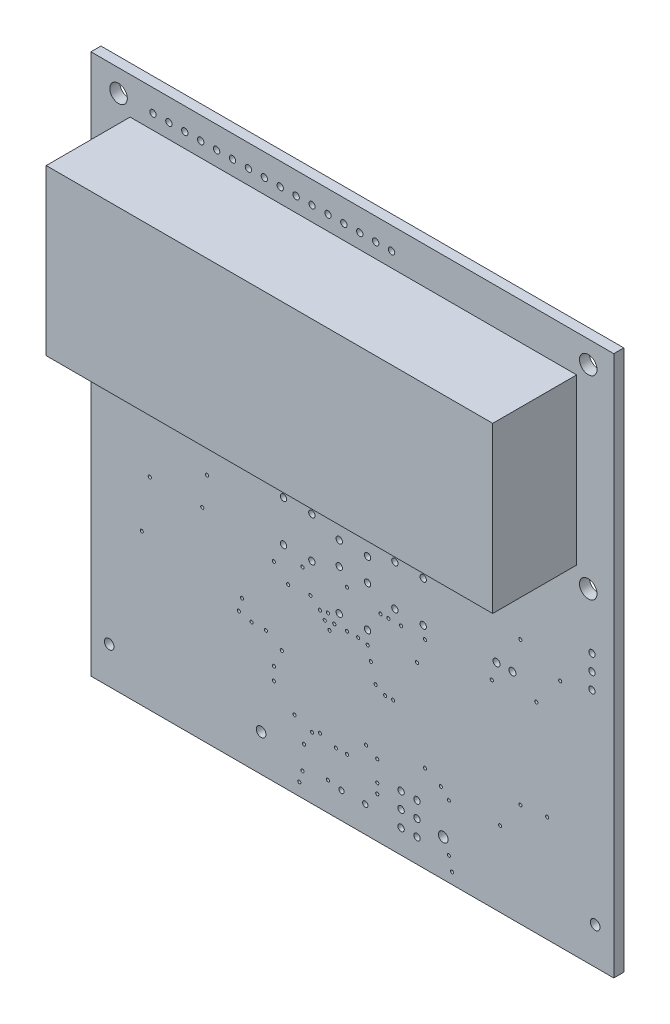
SolidWorks part; units mm, degrees
ref_plane "Front Plane" through (0, 0, 0) normal (0, 0, 1) x (1, 0, 0)
ref_plane "Top Plane" through (0, 0, 0) normal (0, 1, 0) x (1, 0, 0)
ref_plane "Right Plane" through (0, 0, 0) normal (1, 0, 0) x (0, 0, -1)
sketch "20" plane through (0, 0, 0) normal (0, 0, 1) x (1, 0, 0)
  line L0 (0, 86.36) -> (0, 0.02)
  line L1 (0, 0.02) -> (83.49, 0.02)
  line L2 (83.49, 0.02) -> (83.49, 86.36)
  line L3 (83.49, 86.36) -> (0, 86.36)
  circle A1 centre (40.01, 4.232) radius 0.425
  circle A2 centre (43.81, 4.232) radius 0.425
  circle A3 centre (27.18, 5.91) radius 0.775
  circle A4 centre (2.92, 5.91) radius 0.775
  circle A5 centre (80.52, 5.91) radius 0.775
  circle A6 centre (56.26, 5.91) radius 0.775
  circle A7 centre (4.41, 82.81) radius 1.4
  circle A8 centre (4.41, 51.81) radius 1.4
  circle A9 centre (79.41, 82.81) radius 1.4
  circle A10 centre (79.41, 51.81) radius 1.4
sketch "21" plane through (0, 0, 0) normal (0, 0, 1) x (1, 0, 0)
  line L120 (37.9171, 5.014) -> (37.9171, 4.032)
  line L121 (37.9171, 4.032) -> (37.91, 4.032)
  line L122 (37.91, 5.032) -> (38.91, 5.032)
  line L123 (45.91, 4.032) -> (45.91, 5.032)
  line L124 (45.91, 5.032) -> (44.91, 5.032)
  line L125 (37.91, 1.032) -> (37.91, 0.032)
  line L126 (45.91, 1.032) -> (45.91, 0.032)
  line L127 (47.625, 59.69) -> (48.895, 59.69)
  line L128 (48.895, 59.69) -> (49.53, 59.055)
  line L129 (49.53, 57.785) -> (48.895, 57.15)
  line L130 (44.45, 59.055) -> (45.085, 59.69)
  line L131 (45.085, 59.69) -> (46.355, 59.69)
  line L132 (46.355, 59.69) -> (46.99, 59.055)
  line L133 (46.99, 57.785) -> (46.355, 57.15)
  line L134 (46.355, 57.15) -> (45.085, 57.15)
  line L135 (45.085, 57.15) -> (44.45, 57.785)
  line L136 (47.625, 59.69) -> (46.99, 59.055)
  line L137 (46.99, 57.785) -> (47.625, 57.15)
  line L138 (48.895, 57.15) -> (47.625, 57.15)
  line L139 (40.005, 59.69) -> (41.275, 59.69)
  line L140 (41.275, 59.69) -> (41.91, 59.055)
  line L141 (41.91, 57.785) -> (41.275, 57.15)
  line L142 (41.91, 59.055) -> (42.545, 59.69)
  line L143 (42.545, 59.69) -> (43.815, 59.69)
  line L144 (43.815, 59.69) -> (44.45, 59.055)
  line L145 (44.45, 57.785) -> (43.815, 57.15)
  line L146 (43.815, 57.15) -> (42.545, 57.15)
  line L147 (42.545, 57.15) -> (41.91, 57.785)
  line L148 (36.83, 59.055) -> (37.465, 59.69)
  line L149 (37.465, 59.69) -> (38.735, 59.69)
  line L150 (38.735, 59.69) -> (39.37, 59.055)
  line L151 (39.37, 57.785) -> (38.735, 57.15)
  line L152 (38.735, 57.15) -> (37.465, 57.15)
  line L153 (37.465, 57.15) -> (36.83, 57.785)
  line L154 (40.005, 59.69) -> (39.37, 59.055)
  line L155 (39.37, 57.785) -> (40.005, 57.15)
  line L156 (41.275, 57.15) -> (40.005, 57.15)
  line L157 (32.385, 59.69) -> (33.655, 59.69)
  line L158 (33.655, 59.69) -> (34.29, 59.055)
  line L159 (34.29, 57.785) -> (33.655, 57.15)
  line L160 (34.29, 59.055) -> (34.925, 59.69)
  line L161 (34.925, 59.69) -> (36.195, 59.69)
  line L162 (36.195, 59.69) -> (36.83, 59.055)
  line L163 (36.83, 57.785) -> (36.195, 57.15)
  line L164 (36.195, 57.15) -> (34.925, 57.15)
  line L165 (34.925, 57.15) -> (34.29, 57.785)
  line L166 (31.75, 59.055) -> (31.75, 57.785)
  line L167 (32.385, 59.69) -> (31.75, 59.055)
  line L168 (31.75, 57.785) -> (32.385, 57.15)
  line L169 (33.655, 57.15) -> (32.385, 57.15)
  line L170 (50.165, 59.69) -> (51.435, 59.69)
  line L171 (51.435, 59.69) -> (52.07, 59.055)
  line L172 (52.07, 59.055) -> (52.07, 57.785)
  line L173 (52.07, 57.785) -> (51.435, 57.15)
  line L174 (50.165, 59.69) -> (49.53, 59.055)
  line L175 (49.53, 57.785) -> (50.165, 57.15)
  line L176 (51.435, 57.15) -> (50.165, 57.15)
  line L181 (44.958, 29.591) -> (44.958, 33.909)
  line L182 (38.862, 33.909) -> (38.862, 29.591)
  line L183 (42.908, 28.702) -> (40.894, 28.702)
  line L184 (42.938, 34.798) -> (40.894, 34.798)
  line L189 (44.958, 39.751) -> (44.958, 44.069)
  line L190 (38.862, 44.069) -> (38.862, 39.751)
  line L191 (42.908, 38.862) -> (40.894, 38.862)
  line L192 (42.938, 44.958) -> (40.894, 44.958)
  line L193 (53.848, 34.671) -> (53.848, 38.989)
  line L194 (47.752, 38.989) -> (47.752, 34.671)
  line L195 (51.798, 33.782) -> (49.784, 33.782)
  line L196 (51.828, 39.878) -> (49.784, 39.878)
  line L197 (36.068, 34.671) -> (36.068, 38.989)
  line L198 (29.972, 38.989) -> (29.972, 34.671)
  line L199 (34.018, 33.782) -> (32.004, 33.782)
  line L200 (34.048, 39.878) -> (32.004, 39.878)
  line L201 (82.185, 46.455) -> (77.835, 46.455)
  line L202 (77.835, 46.455) -> (77.835, 34.825)
  line L203 (77.835, 34.825) -> (82.185, 34.825)
  line L204 (82.185, 34.825) -> (82.185, 46.455)
  line L268 (25.259, 29.305) -> (29.658, 29.305)
  line L269 (29.658, 29.305) -> (29.658, 23.971)
  line L270 (29.558, 7.361) -> (29.558, 0.322)
  line L271 (29.558, 0.322) -> (28.14, 0.31)
  line L272 (0.913, 6.199) -> (0.913, 0.322)
  line L273 (0.913, 0.322) -> (1.891, 0.322)
  line L274 (1.002, 29.305) -> (0.913, 29.305)
  line L275 (0.913, 29.305) -> (0.913, 23.971)
  line L276 (78.599, 29.305) -> (82.998, 29.305)
  line L277 (82.998, 29.305) -> (82.998, 23.971)
  line L278 (82.898, 7.361) -> (82.898, 0.322)
  line L279 (82.898, 0.322) -> (81.48, 0.31)
  line L280 (54.253, 6.199) -> (54.253, 0.322)
  line L281 (54.253, 0.322) -> (55.231, 0.322)
  line L282 (54.342, 29.305) -> (54.253, 29.305)
  line L283 (54.253, 29.305) -> (54.253, 23.971)
  line L284 (1.91, 85.31) -> (81.91, 85.31)
  line L285 (81.91, 85.31) -> (81.91, 49.31)
  line L286 (81.91, 49.31) -> (1.91, 49.31)
  line L287 (1.91, 49.31) -> (1.91, 85.31)
  line L288 (6.26, 80.46) -> (77.56, 80.46)
  line L289 (77.56, 80.46) -> (77.56, 54.16)
  line L290 (77.56, 54.16) -> (6.26, 54.16)
  line L291 (6.26, 54.16) -> (6.26, 80.46)
  arc A255 (37.8409, 4.032) -> (37.9933, 4.032) centre (37.9171, 4.032) ccw
  arc A256 (37.9933, 5.014) -> (37.8409, 5.014) centre (37.9171, 5.014) ccw
  arc A257 (37.91, 4.1082) -> (37.91, 3.9558) centre (37.91, 4.032) ccw
  arc A258 (37.9171, 3.9558) -> (37.9171, 4.1082) centre (37.9171, 4.032) ccw
  arc A259 (38.91, 4.9558) -> (38.91, 5.1082) centre (38.91, 5.032) ccw
  arc A260 (37.91, 5.1082) -> (37.91, 4.9558) centre (37.91, 5.032) ccw
  arc A261 (45.9862, 5.032) -> (45.8338, 5.032) centre (45.91, 5.032) ccw
  arc A262 (45.8338, 4.032) -> (45.9862, 4.032) centre (45.91, 4.032) ccw
  arc A263 (44.91, 5.1082) -> (44.91, 4.9558) centre (44.91, 5.032) ccw
  arc A264 (45.91, 4.9558) -> (45.91, 5.1082) centre (45.91, 5.032) ccw
  arc A265 (37.8338, 0.032) -> (37.9862, 0.032) centre (37.91, 0.032) ccw
  arc A266 (37.9862, 1.032) -> (37.8338, 1.032) centre (37.91, 1.032) ccw
  arc A267 (45.8338, 0.032) -> (45.9862, 0.032) centre (45.91, 0.032) ccw
  arc A268 (45.9862, 1.032) -> (45.8338, 1.032) centre (45.91, 1.032) ccw
  arc A269 (48.895, 59.6392) -> (48.895, 59.7408) centre (48.895, 59.69) ccw
  arc A270 (47.625, 59.7408) -> (47.625, 59.6392) centre (47.625, 59.69) ccw
  arc A271 (49.4941, 59.0191) -> (49.5659, 59.0909) centre (49.53, 59.055) ccw
  arc A272 (48.9309, 59.7259) -> (48.8591, 59.6541) centre (48.895, 59.69) ccw
  arc A273 (48.8591, 57.1859) -> (48.9309, 57.1141) centre (48.895, 57.15) ccw
  arc A274 (49.5659, 57.7491) -> (49.4941, 57.8209) centre (49.53, 57.785) ccw
  arc A275 (45.1209, 59.6541) -> (45.0491, 59.7259) centre (45.085, 59.69) ccw
  arc A276 (44.4141, 59.0909) -> (44.4859, 59.0191) centre (44.45, 59.055) ccw
  arc A277 (46.355, 59.6392) -> (46.355, 59.7408) centre (46.355, 59.69) ccw
  arc A278 (45.085, 59.7408) -> (45.085, 59.6392) centre (45.085, 59.69) ccw
  arc A279 (46.9541, 59.0191) -> (47.0259, 59.0909) centre (46.99, 59.055) ccw
  arc A280 (46.3909, 59.7259) -> (46.3191, 59.6541) centre (46.355, 59.69) ccw
  arc A281 (46.3191, 57.1859) -> (46.3909, 57.1141) centre (46.355, 57.15) ccw
  arc A282 (47.0259, 57.7491) -> (46.9541, 57.8209) centre (46.99, 57.785) ccw
  arc A283 (45.085, 57.2008) -> (45.085, 57.0992) centre (45.085, 57.15) ccw
  arc A284 (46.355, 57.0992) -> (46.355, 57.2008) centre (46.355, 57.15) ccw
  arc A285 (44.4859, 57.8209) -> (44.4141, 57.7491) centre (44.45, 57.785) ccw
  arc A286 (45.0491, 57.1141) -> (45.1209, 57.1859) centre (45.085, 57.15) ccw
  arc A287 (46.9541, 59.0909) -> (47.0259, 59.0191) centre (46.99, 59.055) ccw
  arc A288 (47.6609, 59.6541) -> (47.5891, 59.7259) centre (47.625, 59.69) ccw
  arc A289 (47.5891, 57.1141) -> (47.6609, 57.1859) centre (47.625, 57.15) ccw
  arc A290 (47.0259, 57.8209) -> (46.9541, 57.7491) centre (46.99, 57.785) ccw
  arc A291 (47.625, 57.2008) -> (47.625, 57.0992) centre (47.625, 57.15) ccw
  arc A292 (48.895, 57.0992) -> (48.895, 57.2008) centre (48.895, 57.15) ccw
  arc A293 (41.275, 59.6392) -> (41.275, 59.7408) centre (41.275, 59.69) ccw
  arc A294 (40.005, 59.7408) -> (40.005, 59.6392) centre (40.005, 59.69) ccw
  arc A295 (41.8741, 59.0191) -> (41.9459, 59.0909) centre (41.91, 59.055) ccw
  arc A296 (41.3109, 59.7259) -> (41.2391, 59.6541) centre (41.275, 59.69) ccw
  arc A297 (41.2391, 57.1859) -> (41.3109, 57.1141) centre (41.275, 57.15) ccw
  arc A298 (41.9459, 57.7491) -> (41.8741, 57.8209) centre (41.91, 57.785) ccw
  arc A299 (42.5809, 59.6541) -> (42.5091, 59.7259) centre (42.545, 59.69) ccw
  arc A300 (41.8741, 59.0909) -> (41.9459, 59.0191) centre (41.91, 59.055) ccw
  arc A301 (43.815, 59.6392) -> (43.815, 59.7408) centre (43.815, 59.69) ccw
  arc A302 (42.545, 59.7408) -> (42.545, 59.6392) centre (42.545, 59.69) ccw
  arc A303 (44.4141, 59.0191) -> (44.4859, 59.0909) centre (44.45, 59.055) ccw
  arc A304 (43.8509, 59.7259) -> (43.7791, 59.6541) centre (43.815, 59.69) ccw
  arc A305 (43.7791, 57.1859) -> (43.8509, 57.1141) centre (43.815, 57.15) ccw
  arc A306 (44.4859, 57.7491) -> (44.4141, 57.8209) centre (44.45, 57.785) ccw
  arc A307 (42.545, 57.2008) -> (42.545, 57.0992) centre (42.545, 57.15) ccw
  arc A308 (43.815, 57.0992) -> (43.815, 57.2008) centre (43.815, 57.15) ccw
  arc A309 (41.9459, 57.8209) -> (41.8741, 57.7491) centre (41.91, 57.785) ccw
  arc A310 (42.5091, 57.1141) -> (42.5809, 57.1859) centre (42.545, 57.15) ccw
  arc A311 (37.5009, 59.6541) -> (37.4291, 59.7259) centre (37.465, 59.69) ccw
  arc A312 (36.7941, 59.0909) -> (36.8659, 59.0191) centre (36.83, 59.055) ccw
  arc A313 (38.735, 59.6392) -> (38.735, 59.7408) centre (38.735, 59.69) ccw
  arc A314 (37.465, 59.7408) -> (37.465, 59.6392) centre (37.465, 59.69) ccw
  arc A315 (39.3341, 59.0191) -> (39.4059, 59.0909) centre (39.37, 59.055) ccw
  arc A316 (38.7709, 59.7259) -> (38.6991, 59.6541) centre (38.735, 59.69) ccw
  arc A317 (38.6991, 57.1859) -> (38.7709, 57.1141) centre (38.735, 57.15) ccw
  arc A318 (39.4059, 57.7491) -> (39.3341, 57.8209) centre (39.37, 57.785) ccw
  arc A319 (37.465, 57.2008) -> (37.465, 57.0992) centre (37.465, 57.15) ccw
  arc A320 (38.735, 57.0992) -> (38.735, 57.2008) centre (38.735, 57.15) ccw
  arc A321 (36.8659, 57.8209) -> (36.7941, 57.7491) centre (36.83, 57.785) ccw
  arc A322 (37.4291, 57.1141) -> (37.5009, 57.1859) centre (37.465, 57.15) ccw
  arc A323 (39.3341, 59.0909) -> (39.4059, 59.0191) centre (39.37, 59.055) ccw
  arc A324 (40.0409, 59.6541) -> (39.9691, 59.7259) centre (40.005, 59.69) ccw
  arc A325 (39.9691, 57.1141) -> (40.0409, 57.1859) centre (40.005, 57.15) ccw
  arc A326 (39.4059, 57.8209) -> (39.3341, 57.7491) centre (39.37, 57.785) ccw
  arc A327 (40.005, 57.2008) -> (40.005, 57.0992) centre (40.005, 57.15) ccw
  arc A328 (41.275, 57.0992) -> (41.275, 57.2008) centre (41.275, 57.15) ccw
  arc A329 (33.655, 59.6392) -> (33.655, 59.7408) centre (33.655, 59.69) ccw
  arc A330 (32.385, 59.7408) -> (32.385, 59.6392) centre (32.385, 59.69) ccw
  arc A331 (34.2541, 59.0191) -> (34.3259, 59.0909) centre (34.29, 59.055) ccw
  arc A332 (33.6909, 59.7259) -> (33.6191, 59.6541) centre (33.655, 59.69) ccw
  arc A333 (33.6191, 57.1859) -> (33.6909, 57.1141) centre (33.655, 57.15) ccw
  arc A334 (34.3259, 57.7491) -> (34.2541, 57.8209) centre (34.29, 57.785) ccw
  arc A335 (34.9609, 59.6541) -> (34.8891, 59.7259) centre (34.925, 59.69) ccw
  arc A336 (34.2541, 59.0909) -> (34.3259, 59.0191) centre (34.29, 59.055) ccw
  arc A337 (36.195, 59.6392) -> (36.195, 59.7408) centre (36.195, 59.69) ccw
  arc A338 (34.925, 59.7408) -> (34.925, 59.6392) centre (34.925, 59.69) ccw
  arc A339 (36.7941, 59.0191) -> (36.8659, 59.0909) centre (36.83, 59.055) ccw
  arc A340 (36.2309, 59.7259) -> (36.1591, 59.6541) centre (36.195, 59.69) ccw
  arc A341 (36.1591, 57.1859) -> (36.2309, 57.1141) centre (36.195, 57.15) ccw
  arc A342 (36.8659, 57.7491) -> (36.7941, 57.8209) centre (36.83, 57.785) ccw
  arc A343 (34.925, 57.2008) -> (34.925, 57.0992) centre (34.925, 57.15) ccw
  arc A344 (36.195, 57.0992) -> (36.195, 57.2008) centre (36.195, 57.15) ccw
  arc A345 (34.3259, 57.8209) -> (34.2541, 57.7491) centre (34.29, 57.785) ccw
  arc A346 (34.8891, 57.1141) -> (34.9609, 57.1859) centre (34.925, 57.15) ccw
  arc A347 (31.6992, 57.785) -> (31.8008, 57.785) centre (31.75, 57.785) ccw
  arc A348 (31.8008, 59.055) -> (31.6992, 59.055) centre (31.75, 59.055) ccw
  arc A349 (31.7141, 59.0909) -> (31.7859, 59.0191) centre (31.75, 59.055) ccw
  arc A350 (32.4209, 59.6541) -> (32.3491, 59.7259) centre (32.385, 59.69) ccw
  arc A351 (32.3491, 57.1141) -> (32.4209, 57.1859) centre (32.385, 57.15) ccw
  arc A352 (31.7859, 57.8209) -> (31.7141, 57.7491) centre (31.75, 57.785) ccw
  arc A353 (32.385, 57.2008) -> (32.385, 57.0992) centre (32.385, 57.15) ccw
  arc A354 (33.655, 57.0992) -> (33.655, 57.2008) centre (33.655, 57.15) ccw
  arc A355 (51.435, 59.6392) -> (51.435, 59.7408) centre (51.435, 59.69) ccw
  arc A356 (50.165, 59.7408) -> (50.165, 59.6392) centre (50.165, 59.69) ccw
  arc A357 (52.0341, 59.0191) -> (52.1059, 59.0909) centre (52.07, 59.055) ccw
  arc A358 (51.4709, 59.7259) -> (51.3991, 59.6541) centre (51.435, 59.69) ccw
  arc A359 (52.0192, 57.785) -> (52.1208, 57.785) centre (52.07, 57.785) ccw
  arc A360 (52.1208, 59.055) -> (52.0192, 59.055) centre (52.07, 59.055) ccw
  arc A361 (51.3991, 57.1859) -> (51.4709, 57.1141) centre (51.435, 57.15) ccw
  arc A362 (52.1059, 57.7491) -> (52.0341, 57.8209) centre (52.07, 57.785) ccw
  arc A363 (49.4941, 59.0909) -> (49.5659, 59.0191) centre (49.53, 59.055) ccw
  arc A364 (50.2009, 59.6541) -> (50.1291, 59.7259) centre (50.165, 59.69) ccw
  arc A365 (50.1291, 57.1141) -> (50.2009, 57.1859) centre (50.165, 57.15) ccw
  arc A366 (49.5659, 57.8209) -> (49.4941, 57.7491) centre (49.53, 57.785) ccw
  arc A367 (50.165, 57.2008) -> (50.165, 57.0992) centre (50.165, 57.15) ccw
  arc A368 (51.435, 57.0992) -> (51.435, 57.2008) centre (51.435, 57.15) ccw
  arc A377 (45.0088, 33.909) -> (44.9072, 33.909) centre (44.958, 33.909) ccw
  arc A378 (44.9072, 29.591) -> (45.0088, 29.591) centre (44.958, 29.591) ccw
  arc A379 (38.8112, 29.591) -> (38.9128, 29.591) centre (38.862, 29.591) ccw
  arc A380 (38.9128, 33.909) -> (38.8112, 33.909) centre (38.862, 33.909) ccw
  arc A381 (40.894, 28.7528) -> (40.894, 28.6512) centre (40.894, 28.702) ccw
  arc A382 (42.908, 28.6512) -> (42.908, 28.7528) centre (42.908, 28.702) ccw
  arc A383 (40.894, 34.8488) -> (40.894, 34.7472) centre (40.894, 34.798) ccw
  arc A384 (42.938, 34.7472) -> (42.938, 34.8488) centre (42.938, 34.798) ccw
  circle A385 centre (41.91, 31.75) radius 1.778
  arc A395 (45.0088, 44.069) -> (44.9072, 44.069) centre (44.958, 44.069) ccw
  arc A396 (44.9072, 39.751) -> (45.0088, 39.751) centre (44.958, 39.751) ccw
  arc A397 (38.8112, 39.751) -> (38.9128, 39.751) centre (38.862, 39.751) ccw
  arc A398 (38.9128, 44.069) -> (38.8112, 44.069) centre (38.862, 44.069) ccw
  arc A399 (40.894, 38.9128) -> (40.894, 38.8112) centre (40.894, 38.862) ccw
  arc A400 (42.908, 38.8112) -> (42.908, 38.9128) centre (42.908, 38.862) ccw
  arc A401 (40.894, 45.0088) -> (40.894, 44.9072) centre (40.894, 44.958) ccw
  arc A402 (42.938, 44.9072) -> (42.938, 45.0088) centre (42.938, 44.958) ccw
  circle A403 centre (41.91, 41.91) radius 1.778
  arc A404 (53.8988, 38.989) -> (53.7972, 38.989) centre (53.848, 38.989) ccw
  arc A405 (53.7972, 34.671) -> (53.8988, 34.671) centre (53.848, 34.671) ccw
  arc A406 (47.7012, 34.671) -> (47.8028, 34.671) centre (47.752, 34.671) ccw
  arc A407 (47.8028, 38.989) -> (47.7012, 38.989) centre (47.752, 38.989) ccw
  arc A408 (49.784, 33.8328) -> (49.784, 33.7312) centre (49.784, 33.782) ccw
  arc A409 (51.798, 33.7312) -> (51.798, 33.8328) centre (51.798, 33.782) ccw
  arc A410 (49.784, 39.9288) -> (49.784, 39.8272) centre (49.784, 39.878) ccw
  arc A411 (51.828, 39.8272) -> (51.828, 39.9288) centre (51.828, 39.878) ccw
  circle A412 centre (50.8, 36.83) radius 1.778
  arc A413 (36.1188, 38.989) -> (36.0172, 38.989) centre (36.068, 38.989) ccw
  arc A414 (36.0172, 34.671) -> (36.1188, 34.671) centre (36.068, 34.671) ccw
  arc A415 (29.9212, 34.671) -> (30.0228, 34.671) centre (29.972, 34.671) ccw
  arc A416 (30.0228, 38.989) -> (29.9212, 38.989) centre (29.972, 38.989) ccw
  arc A417 (32.004, 33.8328) -> (32.004, 33.7312) centre (32.004, 33.782) ccw
  arc A418 (34.018, 33.7312) -> (34.018, 33.8328) centre (34.018, 33.782) ccw
  arc A419 (32.004, 39.9288) -> (32.004, 39.8272) centre (32.004, 39.878) ccw
  arc A420 (34.048, 39.8272) -> (34.048, 39.9288) centre (34.048, 39.878) ccw
  circle A421 centre (33.02, 36.83) radius 1.778
  arc A422 (77.835, 46.5058) -> (77.835, 46.4042) centre (77.835, 46.455) ccw
  arc A423 (82.185, 46.4042) -> (82.185, 46.5058) centre (82.185, 46.455) ccw
  arc A424 (77.7842, 34.825) -> (77.8858, 34.825) centre (77.835, 34.825) ccw
  arc A425 (77.8858, 46.455) -> (77.7842, 46.455) centre (77.835, 46.455) ccw
  arc A426 (82.185, 34.7742) -> (82.185, 34.8758) centre (82.185, 34.825) ccw
  arc A427 (77.835, 34.8758) -> (77.835, 34.7742) centre (77.835, 34.825) ccw
  arc A428 (82.2358, 46.455) -> (82.1342, 46.455) centre (82.185, 46.455) ccw
  arc A429 (82.1342, 34.825) -> (82.2358, 34.825) centre (82.185, 34.825) ccw
  arc A569 (29.658, 29.2415) -> (29.658, 29.3685) centre (29.658, 29.305) ccw
  arc A570 (25.259, 29.3685) -> (25.259, 29.2415) centre (25.259, 29.305) ccw
  arc A571 (29.5945, 23.971) -> (29.7215, 23.971) centre (29.658, 23.971) ccw
  arc A572 (29.7215, 29.305) -> (29.5945, 29.305) centre (29.658, 29.305) ccw
  arc A573 (29.4945, 0.322) -> (29.6215, 0.322) centre (29.558, 0.322) ccw
  arc A574 (29.6215, 7.361) -> (29.4945, 7.361) centre (29.558, 7.361) ccw
  arc A575 (28.1395, 0.3735) -> (28.1405, 0.2465) centre (28.14, 0.31) ccw
  arc A576 (29.5585, 0.2585) -> (29.5575, 0.3855) centre (29.558, 0.322) ccw
  arc A577 (0.8495, 0.322) -> (0.9765, 0.322) centre (0.913, 0.322) ccw
  arc A578 (0.9765, 6.199) -> (0.8495, 6.199) centre (0.913, 6.199) ccw
  arc A579 (1.891, 0.2585) -> (1.891, 0.3855) centre (1.891, 0.322) ccw
  arc A580 (0.913, 0.3855) -> (0.913, 0.2585) centre (0.913, 0.322) ccw
  arc A581 (0.913, 29.3685) -> (0.913, 29.2415) centre (0.913, 29.305) ccw
  arc A582 (1.002, 29.2415) -> (1.002, 29.3685) centre (1.002, 29.305) ccw
  arc A583 (0.8495, 23.971) -> (0.9765, 23.971) centre (0.913, 23.971) ccw
  arc A584 (0.9765, 29.305) -> (0.8495, 29.305) centre (0.913, 29.305) ccw
  arc A585 (82.998, 29.2415) -> (82.998, 29.3685) centre (82.998, 29.305) ccw
  arc A586 (78.599, 29.3685) -> (78.599, 29.2415) centre (78.599, 29.305) ccw
  arc A587 (82.9345, 23.971) -> (83.0615, 23.971) centre (82.998, 23.971) ccw
  arc A588 (83.0615, 29.305) -> (82.9345, 29.305) centre (82.998, 29.305) ccw
  arc A589 (82.8345, 0.322) -> (82.9615, 0.322) centre (82.898, 0.322) ccw
  arc A590 (82.9615, 7.361) -> (82.8345, 7.361) centre (82.898, 7.361) ccw
  arc A591 (81.4795, 0.3735) -> (81.4805, 0.2465) centre (81.48, 0.31) ccw
  arc A592 (82.8985, 0.2585) -> (82.8975, 0.3855) centre (82.898, 0.322) ccw
  arc A593 (54.1895, 0.322) -> (54.3165, 0.322) centre (54.253, 0.322) ccw
  arc A594 (54.3165, 6.199) -> (54.1895, 6.199) centre (54.253, 6.199) ccw
  arc A595 (55.231, 0.2585) -> (55.231, 0.3855) centre (55.231, 0.322) ccw
  arc A596 (54.253, 0.3855) -> (54.253, 0.2585) centre (54.253, 0.322) ccw
  arc A597 (54.253, 29.3685) -> (54.253, 29.2415) centre (54.253, 29.305) ccw
  arc A598 (54.342, 29.2415) -> (54.342, 29.3685) centre (54.342, 29.305) ccw
  arc A599 (54.1895, 23.971) -> (54.3165, 23.971) centre (54.253, 23.971) ccw
  arc A600 (54.3165, 29.305) -> (54.1895, 29.305) centre (54.253, 29.305) ccw
  arc A601 (81.91, 85.2592) -> (81.91, 85.3608) centre (81.91, 85.31) ccw
  arc A602 (1.91, 85.3608) -> (1.91, 85.2592) centre (1.91, 85.31) ccw
  arc A603 (81.8592, 49.31) -> (81.9608, 49.31) centre (81.91, 49.31) ccw
  arc A604 (81.9608, 85.31) -> (81.8592, 85.31) centre (81.91, 85.31) ccw
  arc A605 (1.91, 49.3608) -> (1.91, 49.2592) centre (1.91, 49.31) ccw
  arc A606 (81.91, 49.2592) -> (81.91, 49.3608) centre (81.91, 49.31) ccw
  arc A607 (1.9608, 85.31) -> (1.8592, 85.31) centre (1.91, 85.31) ccw
  arc A608 (1.8592, 49.31) -> (1.9608, 49.31) centre (1.91, 49.31) ccw
  arc A609 (77.56, 80.4092) -> (77.56, 80.5108) centre (77.56, 80.46) ccw
  arc A610 (6.26, 80.5108) -> (6.26, 80.4092) centre (6.26, 80.46) ccw
  arc A611 (77.5092, 54.16) -> (77.6108, 54.16) centre (77.56, 54.16) ccw
  arc A612 (77.6108, 80.46) -> (77.5092, 80.46) centre (77.56, 80.46) ccw
  arc A613 (6.26, 54.2108) -> (6.26, 54.1092) centre (6.26, 54.16) ccw
  arc A614 (77.56, 54.1092) -> (77.56, 54.2108) centre (77.56, 54.16) ccw
  arc A615 (6.3108, 80.46) -> (6.2092, 80.46) centre (6.26, 80.46) ccw
  arc A616 (6.2092, 54.16) -> (6.3108, 54.16) centre (6.26, 54.16) ccw
sketch "51" plane through (0, 0, 0) normal (0, 0, 1) x (1, 0, 0)
  line L199 (42.926, 28.702) -> (44.45, 28.702)
  line L200 (44.45, 28.702) -> (44.958, 29.21)
  line L201 (38.862, 29.21) -> (39.37, 28.702)
  line L202 (39.37, 28.702) -> (40.894, 28.702)
  line L203 (44.958, 34.29) -> (44.45, 34.798)
  line L204 (44.45, 34.798) -> (42.926, 34.798)
  line L205 (38.862, 34.29) -> (39.37, 34.798)
  line L206 (39.37, 34.798) -> (40.894, 34.798)
  line L207 (38.862, 29.21) -> (38.862, 29.591)
  line L208 (38.862, 34.29) -> (38.862, 33.909)
  line L209 (44.958, 34.29) -> (44.958, 33.909)
  line L210 (44.958, 29.21) -> (44.958, 29.591)
  line L211 (43.18, 34.29) -> (42.418, 34.29)
  line L212 (41.402, 34.29) -> (40.64, 34.29)
  line L213 (42.418, 34.29) -> (41.529, 33.909)
  line L221 (42.926, 38.862) -> (44.45, 38.862)
  line L222 (44.45, 38.862) -> (44.958, 39.37)
  line L223 (38.862, 39.37) -> (39.37, 38.862)
  line L224 (39.37, 38.862) -> (40.894, 38.862)
  line L225 (44.958, 44.45) -> (44.45, 44.958)
  line L226 (44.45, 44.958) -> (42.926, 44.958)
  line L227 (38.862, 44.45) -> (39.37, 44.958)
  line L228 (39.37, 44.958) -> (40.894, 44.958)
  line L229 (38.862, 39.37) -> (38.862, 39.751)
  line L230 (38.862, 44.45) -> (38.862, 44.069)
  line L231 (44.958, 44.45) -> (44.958, 44.069)
  line L232 (44.958, 39.37) -> (44.958, 39.751)
  line L233 (43.18, 44.45) -> (42.418, 44.45)
  line L234 (41.402, 44.45) -> (40.64, 44.45)
  line L235 (42.418, 44.45) -> (41.529, 44.069)
  line L236 (51.816, 33.782) -> (53.34, 33.782)
  line L237 (53.34, 33.782) -> (53.848, 34.29)
  line L238 (47.752, 34.29) -> (48.26, 33.782)
  line L239 (48.26, 33.782) -> (49.784, 33.782)
  line L240 (53.848, 39.37) -> (53.34, 39.878)
  line L241 (53.34, 39.878) -> (51.816, 39.878)
  line L242 (47.752, 39.37) -> (48.26, 39.878)
  line L243 (48.26, 39.878) -> (49.784, 39.878)
  line L244 (47.752, 34.29) -> (47.752, 34.671)
  line L245 (47.752, 39.37) -> (47.752, 38.989)
  line L246 (53.848, 39.37) -> (53.848, 38.989)
  line L247 (53.848, 34.29) -> (53.848, 34.671)
  line L248 (52.07, 39.37) -> (51.308, 39.37)
  line L249 (50.292, 39.37) -> (49.53, 39.37)
  line L250 (51.308, 39.37) -> (50.419, 38.989)
  line L251 (34.036, 33.782) -> (35.56, 33.782)
  line L252 (35.56, 33.782) -> (36.068, 34.29)
  line L253 (29.972, 34.29) -> (30.48, 33.782)
  line L254 (30.48, 33.782) -> (32.004, 33.782)
  line L255 (36.068, 39.37) -> (35.56, 39.878)
  line L256 (35.56, 39.878) -> (34.036, 39.878)
  line L257 (29.972, 39.37) -> (30.48, 39.878)
  line L258 (30.48, 39.878) -> (32.004, 39.878)
  line L259 (29.972, 34.29) -> (29.972, 34.671)
  line L260 (29.972, 39.37) -> (29.972, 38.989)
  line L261 (36.068, 39.37) -> (36.068, 38.989)
  line L262 (36.068, 34.29) -> (36.068, 34.671)
  line L263 (34.29, 39.37) -> (33.528, 39.37)
  line L264 (32.512, 39.37) -> (31.75, 39.37)
  line L265 (33.528, 39.37) -> (32.639, 38.989)
  line L270 (29.49, 29.21) -> (29.49, 0.41)
  line L271 (29.49, 0.41) -> (25.24, 0.41)
  line L272 (25.24, 0.41) -> (4.74, 0.41)
  line L273 (4.74, 0.41) -> (0.99, 0.41)
  line L274 (0.99, 0.41) -> (0.99, 29.21)
  line L275 (0.99, 29.21) -> (29.49, 29.21)
  line L276 (27.24, -6.39) -> (2.24, -6.39)
  line L277 (25.24, 0.41) -> (25.24, 1.21)
  line L278 (15.24, 11.21) -> (14.74, 11.21)
  line L279 (4.74, 1.21) -> (4.74, 0.41)
  line L280 (6.7704, -4.8596) -> (6.1857, -4.8596)
  line L281 (6.1857, -4.8596) -> (5.9908, -5.0545)
  line L282 (5.9908, -5.0545) -> (5.9908, -5.4443)
  line L283 (5.9908, -5.4443) -> (6.1857, -5.6392)
  line L284 (6.1857, -5.6392) -> (6.7704, -5.6392)
  line L285 (7.3551, -4.8596) -> (7.7449, -4.8596)
  line L286 (7.7449, -4.8596) -> (7.9398, -5.0545)
  line L287 (7.9398, -5.0545) -> (7.9398, -5.6392)
  line L288 (7.9398, -5.6392) -> (7.3551, -5.6392)
  line L289 (7.3551, -5.6392) -> (7.1602, -5.4443)
  line L290 (7.1602, -5.4443) -> (7.3551, -5.2494)
  line L291 (7.3551, -5.2494) -> (7.9398, -5.2494)
  line L292 (8.3296, -5.6392) -> (8.3296, -4.8596)
  line L293 (8.3296, -5.2494) -> (8.7194, -4.8596)
  line L294 (8.7194, -4.8596) -> (8.9143, -4.8596)
  line L295 (10.0837, -4.4698) -> (10.0837, -5.6392)
  line L296 (10.0837, -5.6392) -> (9.499, -5.6392)
  line L297 (9.499, -5.6392) -> (9.3041, -5.4443)
  line L298 (9.3041, -5.4443) -> (9.3041, -5.0545)
  line L299 (9.3041, -5.0545) -> (9.499, -4.8596)
  line L300 (9.499, -4.8596) -> (10.0837, -4.8596)
  line L301 (11.6429, -4.4698) -> (11.8378, -4.4698)
  line L302 (11.8378, -4.4698) -> (11.8378, -5.6392)
  line L303 (11.6429, -5.6392) -> (12.0327, -5.6392)
  line L304 (12.6174, -5.6392) -> (13.0072, -5.6392)
  line L305 (13.0072, -5.6392) -> (13.2021, -5.4443)
  line L306 (13.2021, -5.4443) -> (13.2021, -5.0545)
  line L307 (13.2021, -5.0545) -> (13.0072, -4.8596)
  line L308 (13.0072, -4.8596) -> (12.6174, -4.8596)
  line L309 (12.6174, -4.8596) -> (12.4225, -5.0545)
  line L310 (12.4225, -5.0545) -> (12.4225, -5.4443)
  line L311 (12.4225, -5.4443) -> (12.6174, -5.6392)
  line L312 (14.3715, -4.8596) -> (13.7868, -4.8596)
  line L313 (13.7868, -4.8596) -> (13.5919, -5.0545)
  line L314 (13.5919, -5.0545) -> (13.5919, -5.4443)
  line L315 (13.5919, -5.4443) -> (13.7868, -5.6392)
  line L316 (13.7868, -5.6392) -> (14.3715, -5.6392)
  line L317 (14.7613, -5.6392) -> (14.7613, -4.4698)
  line L318 (15.346, -5.6392) -> (14.7613, -5.2494)
  line L319 (14.7613, -5.2494) -> (15.346, -4.8596)
  line L320 (16.9052, -6.029) -> (16.9052, -4.8596)
  line L321 (16.9052, -4.8596) -> (17.4899, -4.8596)
  line L322 (17.4899, -4.8596) -> (17.6848, -5.0545)
  line L323 (17.6848, -5.0545) -> (17.6848, -5.4443)
  line L324 (17.6848, -5.4443) -> (17.4899, -5.6392)
  line L325 (17.4899, -5.6392) -> (16.9052, -5.6392)
  line L326 (18.2695, -5.6392) -> (18.6593, -5.6392)
  line L327 (18.6593, -5.6392) -> (18.8542, -5.4443)
  line L328 (18.8542, -5.4443) -> (18.8542, -5.0545)
  line L329 (18.8542, -5.0545) -> (18.6593, -4.8596)
  line L330 (18.6593, -4.8596) -> (18.2695, -4.8596)
  line L331 (18.2695, -4.8596) -> (18.0746, -5.0545)
  line L332 (18.0746, -5.0545) -> (18.0746, -5.4443)
  line L333 (18.0746, -5.4443) -> (18.2695, -5.6392)
  line L334 (19.244, -5.6392) -> (19.8287, -5.6392)
  line L335 (19.8287, -5.6392) -> (20.0236, -5.4443)
  line L336 (20.0236, -5.4443) -> (19.8287, -5.2494)
  line L337 (19.8287, -5.2494) -> (19.4389, -5.2494)
  line L338 (19.4389, -5.2494) -> (19.244, -5.0545)
  line L339 (19.244, -5.0545) -> (19.4389, -4.8596)
  line L340 (19.4389, -4.8596) -> (20.0236, -4.8596)
  line L341 (20.4134, -4.8596) -> (20.6083, -4.8596)
  line L342 (20.6083, -4.8596) -> (20.6083, -5.6392)
  line L343 (20.4134, -5.6392) -> (20.8032, -5.6392)
  line L344 (20.6083, -4.2749) -> (20.6083, -4.4698)
  line L345 (21.3879, -4.6647) -> (21.3879, -5.4443)
  line L346 (21.3879, -5.4443) -> (21.5828, -5.6392)
  line L347 (21.193, -4.8596) -> (21.5828, -4.8596)
  line L348 (21.9726, -4.8596) -> (22.1675, -4.8596)
  line L349 (22.1675, -4.8596) -> (22.1675, -5.6392)
  line L350 (21.9726, -5.6392) -> (22.3624, -5.6392)
  line L351 (22.1675, -4.2749) -> (22.1675, -4.4698)
  line L352 (22.947, -5.6392) -> (23.3368, -5.6392)
  line L353 (23.3368, -5.6392) -> (23.5317, -5.4443)
  line L354 (23.5317, -5.4443) -> (23.5317, -5.0545)
  line L355 (23.5317, -5.0545) -> (23.3368, -4.8596)
  line L356 (23.3368, -4.8596) -> (22.947, -4.8596)
  line L357 (22.947, -4.8596) -> (22.7522, -5.0545)
  line L358 (22.7522, -5.0545) -> (22.7522, -5.4443)
  line L359 (22.7522, -5.4443) -> (22.947, -5.6392)
  line L360 (23.9215, -5.6392) -> (23.9215, -4.8596)
  line L361 (23.9215, -4.8596) -> (24.5062, -4.8596)
  line L362 (24.5062, -4.8596) -> (24.7011, -5.0545)
  line L363 (24.7011, -5.0545) -> (24.7011, -5.6392)
  line L364 (82.83, 29.21) -> (82.83, 0.41)
  line L365 (82.83, 0.41) -> (78.58, 0.41)
  line L366 (78.58, 0.41) -> (58.08, 0.41)
  line L367 (58.08, 0.41) -> (54.33, 0.41)
  line L368 (54.33, 0.41) -> (54.33, 29.21)
  line L369 (54.33, 29.21) -> (82.83, 29.21)
  line L370 (80.58, -6.39) -> (55.58, -6.39)
  line L371 (78.58, 0.41) -> (78.58, 1.21)
  line L372 (68.58, 11.21) -> (68.08, 11.21)
  line L373 (58.08, 1.21) -> (58.08, 0.41)
  line L374 (60.1104, -4.8596) -> (59.5257, -4.8596)
  line L375 (59.5257, -4.8596) -> (59.3308, -5.0545)
  line L376 (59.3308, -5.0545) -> (59.3308, -5.4443)
  line L377 (59.3308, -5.4443) -> (59.5257, -5.6392)
  line L378 (59.5257, -5.6392) -> (60.1104, -5.6392)
  line L379 (60.6951, -4.8596) -> (61.0849, -4.8596)
  line L380 (61.0849, -4.8596) -> (61.2798, -5.0545)
  line L381 (61.2798, -5.0545) -> (61.2798, -5.6392)
  line L382 (61.2798, -5.6392) -> (60.6951, -5.6392)
  line L383 (60.6951, -5.6392) -> (60.5002, -5.4443)
  line L384 (60.5002, -5.4443) -> (60.6951, -5.2494)
  line L385 (60.6951, -5.2494) -> (61.2798, -5.2494)
  line L386 (61.6696, -5.6392) -> (61.6696, -4.8596)
  line L387 (61.6696, -5.2494) -> (62.0594, -4.8596)
  line L388 (62.0594, -4.8596) -> (62.2543, -4.8596)
  line L389 (63.4237, -4.4698) -> (63.4237, -5.6392)
  line L390 (63.4237, -5.6392) -> (62.839, -5.6392)
  line L391 (62.839, -5.6392) -> (62.6441, -5.4443)
  line L392 (62.6441, -5.4443) -> (62.6441, -5.0545)
  line L393 (62.6441, -5.0545) -> (62.839, -4.8596)
  line L394 (62.839, -4.8596) -> (63.4237, -4.8596)
  line L395 (64.9829, -4.4698) -> (65.1778, -4.4698)
  line L396 (65.1778, -4.4698) -> (65.1778, -5.6392)
  line L397 (64.9829, -5.6392) -> (65.3727, -5.6392)
  line L398 (65.9574, -5.6392) -> (66.3472, -5.6392)
  line L399 (66.3472, -5.6392) -> (66.5421, -5.4443)
  line L400 (66.5421, -5.4443) -> (66.5421, -5.0545)
  line L401 (66.5421, -5.0545) -> (66.3472, -4.8596)
  line L402 (66.3472, -4.8596) -> (65.9574, -4.8596)
  line L403 (65.9574, -4.8596) -> (65.7625, -5.0545)
  line L404 (65.7625, -5.0545) -> (65.7625, -5.4443)
  line L405 (65.7625, -5.4443) -> (65.9574, -5.6392)
  line L406 (67.7115, -4.8596) -> (67.1268, -4.8596)
  line L407 (67.1268, -4.8596) -> (66.9319, -5.0545)
  line L408 (66.9319, -5.0545) -> (66.9319, -5.4443)
  line L409 (66.9319, -5.4443) -> (67.1268, -5.6392)
  line L410 (67.1268, -5.6392) -> (67.7115, -5.6392)
  line L411 (68.1013, -5.6392) -> (68.1013, -4.4698)
  line L412 (68.686, -5.6392) -> (68.1013, -5.2494)
  line L413 (68.1013, -5.2494) -> (68.686, -4.8596)
  line L414 (70.2452, -6.029) -> (70.2452, -4.8596)
  line L415 (70.2452, -4.8596) -> (70.8299, -4.8596)
  line L416 (70.8299, -4.8596) -> (71.0248, -5.0545)
  line L417 (71.0248, -5.0545) -> (71.0248, -5.4443)
  line L418 (71.0248, -5.4443) -> (70.8299, -5.6392)
  line L419 (70.8299, -5.6392) -> (70.2452, -5.6392)
  line L420 (71.6095, -5.6392) -> (71.9993, -5.6392)
  line L421 (71.9993, -5.6392) -> (72.1942, -5.4443)
  line L422 (72.1942, -5.4443) -> (72.1942, -5.0545)
  line L423 (72.1942, -5.0545) -> (71.9993, -4.8596)
  line L424 (71.9993, -4.8596) -> (71.6095, -4.8596)
  line L425 (71.6095, -4.8596) -> (71.4146, -5.0545)
  line L426 (71.4146, -5.0545) -> (71.4146, -5.4443)
  line L427 (71.4146, -5.4443) -> (71.6095, -5.6392)
  line L428 (72.584, -5.6392) -> (73.1687, -5.6392)
  line L429 (73.1687, -5.6392) -> (73.3636, -5.4443)
  line L430 (73.3636, -5.4443) -> (73.1687, -5.2494)
  line L431 (73.1687, -5.2494) -> (72.7789, -5.2494)
  line L432 (72.7789, -5.2494) -> (72.584, -5.0545)
  line L433 (72.584, -5.0545) -> (72.7789, -4.8596)
  line L434 (72.7789, -4.8596) -> (73.3636, -4.8596)
  line L435 (73.7534, -4.8596) -> (73.9483, -4.8596)
  line L436 (73.9483, -4.8596) -> (73.9483, -5.6392)
  line L437 (73.7534, -5.6392) -> (74.1432, -5.6392)
  line L438 (73.9483, -4.2749) -> (73.9483, -4.4698)
  line L439 (74.7279, -4.6647) -> (74.7279, -5.4443)
  line L440 (74.7279, -5.4443) -> (74.9228, -5.6392)
  line L441 (74.533, -4.8596) -> (74.9228, -4.8596)
  line L442 (75.3126, -4.8596) -> (75.5075, -4.8596)
  line L443 (75.5075, -4.8596) -> (75.5075, -5.6392)
  line L444 (75.3126, -5.6392) -> (75.7024, -5.6392)
  line L445 (75.5075, -4.2749) -> (75.5075, -4.4698)
  line L446 (76.287, -5.6392) -> (76.6768, -5.6392)
  line L447 (76.6768, -5.6392) -> (76.8717, -5.4443)
  line L448 (76.8717, -5.4443) -> (76.8717, -5.0545)
  line L449 (76.8717, -5.0545) -> (76.6768, -4.8596)
  line L450 (76.6768, -4.8596) -> (76.287, -4.8596)
  line L451 (76.287, -4.8596) -> (76.0922, -5.0545)
  line L452 (76.0922, -5.0545) -> (76.0922, -5.4443)
  line L453 (76.0922, -5.4443) -> (76.287, -5.6392)
  line L454 (77.2615, -5.6392) -> (77.2615, -4.8596)
  line L455 (77.2615, -4.8596) -> (77.8462, -4.8596)
  line L456 (77.8462, -4.8596) -> (78.0411, -5.0545)
  line L457 (78.0411, -5.0545) -> (78.0411, -5.6392)
  arc A398 (44.45, 28.6512) -> (44.45, 28.7528) centre (44.45, 28.702) ccw
  arc A399 (42.926, 28.7528) -> (42.926, 28.6512) centre (42.926, 28.702) ccw
  arc A400 (44.9939, 29.1741) -> (44.9221, 29.2459) centre (44.958, 29.21) ccw
  arc A401 (44.4141, 28.7379) -> (44.4859, 28.6661) centre (44.45, 28.702) ccw
  arc A402 (39.3341, 28.6661) -> (39.4059, 28.7379) centre (39.37, 28.702) ccw
  arc A403 (38.8979, 29.2459) -> (38.8261, 29.1741) centre (38.862, 29.21) ccw
  arc A404 (40.894, 28.6512) -> (40.894, 28.7528) centre (40.894, 28.702) ccw
  arc A405 (39.37, 28.7528) -> (39.37, 28.6512) centre (39.37, 28.702) ccw
  arc A406 (44.4859, 34.8339) -> (44.4141, 34.7621) centre (44.45, 34.798) ccw
  arc A407 (44.9221, 34.2541) -> (44.9939, 34.3259) centre (44.958, 34.29) ccw
  arc A408 (42.926, 34.8488) -> (42.926, 34.7472) centre (42.926, 34.798) ccw
  arc A409 (44.45, 34.7472) -> (44.45, 34.8488) centre (44.45, 34.798) ccw
  arc A410 (39.4059, 34.7621) -> (39.3341, 34.8339) centre (39.37, 34.798) ccw
  arc A411 (38.8261, 34.3259) -> (38.8979, 34.2541) centre (38.862, 34.29) ccw
  arc A412 (40.894, 34.7472) -> (40.894, 34.8488) centre (40.894, 34.798) ccw
  arc A413 (39.37, 34.8488) -> (39.37, 34.7472) centre (39.37, 34.798) ccw
  arc A414 (38.9128, 29.591) -> (38.8112, 29.591) centre (38.862, 29.591) ccw
  arc A415 (38.8112, 29.21) -> (38.9128, 29.21) centre (38.862, 29.21) ccw
  arc A416 (38.8112, 33.909) -> (38.9128, 33.909) centre (38.862, 33.909) ccw
  arc A417 (38.9128, 34.29) -> (38.8112, 34.29) centre (38.862, 34.29) ccw
  arc A418 (44.9072, 33.909) -> (45.0088, 33.909) centre (44.958, 33.909) ccw
  arc A419 (45.0088, 34.29) -> (44.9072, 34.29) centre (44.958, 34.29) ccw
  arc A420 (45.0088, 29.591) -> (44.9072, 29.591) centre (44.958, 29.591) ccw
  arc A421 (44.9072, 29.21) -> (45.0088, 29.21) centre (44.958, 29.21) ccw
  arc A422 (42.418, 34.3408) -> (42.418, 34.2392) centre (42.418, 34.29) ccw
  arc A423 (43.18, 34.2392) -> (43.18, 34.3408) centre (43.18, 34.29) ccw
  arc A424 (40.64, 34.3408) -> (40.64, 34.2392) centre (40.64, 34.29) ccw
  arc A425 (41.402, 34.2392) -> (41.402, 34.3408) centre (41.402, 34.29) ccw
  arc A426 (41.509, 33.9557) -> (41.549, 33.8623) centre (41.529, 33.909) ccw
  arc A427 (42.438, 34.2433) -> (42.398, 34.3367) centre (42.418, 34.29) ccw
  arc A442 (44.45, 38.8112) -> (44.45, 38.9128) centre (44.45, 38.862) ccw
  arc A443 (42.926, 38.9128) -> (42.926, 38.8112) centre (42.926, 38.862) ccw
  arc A444 (44.9939, 39.3341) -> (44.9221, 39.4059) centre (44.958, 39.37) ccw
  arc A445 (44.4141, 38.8979) -> (44.4859, 38.8261) centre (44.45, 38.862) ccw
  arc A446 (39.3341, 38.8261) -> (39.4059, 38.8979) centre (39.37, 38.862) ccw
  arc A447 (38.8979, 39.4059) -> (38.8261, 39.3341) centre (38.862, 39.37) ccw
  arc A448 (40.894, 38.8112) -> (40.894, 38.9128) centre (40.894, 38.862) ccw
  arc A449 (39.37, 38.9128) -> (39.37, 38.8112) centre (39.37, 38.862) ccw
  arc A450 (44.4859, 44.9939) -> (44.4141, 44.9221) centre (44.45, 44.958) ccw
  arc A451 (44.9221, 44.4141) -> (44.9939, 44.4859) centre (44.958, 44.45) ccw
  arc A452 (42.926, 45.0088) -> (42.926, 44.9072) centre (42.926, 44.958) ccw
  arc A453 (44.45, 44.9072) -> (44.45, 45.0088) centre (44.45, 44.958) ccw
  arc A454 (39.4059, 44.9221) -> (39.3341, 44.9939) centre (39.37, 44.958) ccw
  arc A455 (38.8261, 44.4859) -> (38.8979, 44.4141) centre (38.862, 44.45) ccw
  arc A456 (40.894, 44.9072) -> (40.894, 45.0088) centre (40.894, 44.958) ccw
  arc A457 (39.37, 45.0088) -> (39.37, 44.9072) centre (39.37, 44.958) ccw
  arc A458 (38.9128, 39.751) -> (38.8112, 39.751) centre (38.862, 39.751) ccw
  arc A459 (38.8112, 39.37) -> (38.9128, 39.37) centre (38.862, 39.37) ccw
  arc A460 (38.8112, 44.069) -> (38.9128, 44.069) centre (38.862, 44.069) ccw
  arc A461 (38.9128, 44.45) -> (38.8112, 44.45) centre (38.862, 44.45) ccw
  arc A462 (44.9072, 44.069) -> (45.0088, 44.069) centre (44.958, 44.069) ccw
  arc A463 (45.0088, 44.45) -> (44.9072, 44.45) centre (44.958, 44.45) ccw
  arc A464 (45.0088, 39.751) -> (44.9072, 39.751) centre (44.958, 39.751) ccw
  arc A465 (44.9072, 39.37) -> (45.0088, 39.37) centre (44.958, 39.37) ccw
  arc A466 (42.418, 44.5008) -> (42.418, 44.3992) centre (42.418, 44.45) ccw
  arc A467 (43.18, 44.3992) -> (43.18, 44.5008) centre (43.18, 44.45) ccw
  arc A468 (40.64, 44.5008) -> (40.64, 44.3992) centre (40.64, 44.45) ccw
  arc A469 (41.402, 44.3992) -> (41.402, 44.5008) centre (41.402, 44.45) ccw
  arc A470 (41.509, 44.1157) -> (41.549, 44.0223) centre (41.529, 44.069) ccw
  arc A471 (42.438, 44.4033) -> (42.398, 44.4967) centre (42.418, 44.45) ccw
  arc A472 (53.34, 33.7312) -> (53.34, 33.8328) centre (53.34, 33.782) ccw
  arc A473 (51.816, 33.8328) -> (51.816, 33.7312) centre (51.816, 33.782) ccw
  arc A474 (53.8839, 34.2541) -> (53.8121, 34.3259) centre (53.848, 34.29) ccw
  arc A475 (53.3041, 33.8179) -> (53.3759, 33.7461) centre (53.34, 33.782) ccw
  arc A476 (48.2241, 33.7461) -> (48.2959, 33.8179) centre (48.26, 33.782) ccw
  arc A477 (47.7879, 34.3259) -> (47.7161, 34.2541) centre (47.752, 34.29) ccw
  arc A478 (49.784, 33.7312) -> (49.784, 33.8328) centre (49.784, 33.782) ccw
  arc A479 (48.26, 33.8328) -> (48.26, 33.7312) centre (48.26, 33.782) ccw
  arc A480 (53.3759, 39.9139) -> (53.3041, 39.8421) centre (53.34, 39.878) ccw
  arc A481 (53.8121, 39.3341) -> (53.8839, 39.4059) centre (53.848, 39.37) ccw
  arc A482 (51.816, 39.9288) -> (51.816, 39.8272) centre (51.816, 39.878) ccw
  arc A483 (53.34, 39.8272) -> (53.34, 39.9288) centre (53.34, 39.878) ccw
  arc A484 (48.2959, 39.8421) -> (48.2241, 39.9139) centre (48.26, 39.878) ccw
  arc A485 (47.7161, 39.4059) -> (47.7879, 39.3341) centre (47.752, 39.37) ccw
  arc A486 (49.784, 39.8272) -> (49.784, 39.9288) centre (49.784, 39.878) ccw
  arc A487 (48.26, 39.9288) -> (48.26, 39.8272) centre (48.26, 39.878) ccw
  arc A488 (47.8028, 34.671) -> (47.7012, 34.671) centre (47.752, 34.671) ccw
  arc A489 (47.7012, 34.29) -> (47.8028, 34.29) centre (47.752, 34.29) ccw
  arc A490 (47.7012, 38.989) -> (47.8028, 38.989) centre (47.752, 38.989) ccw
  arc A491 (47.8028, 39.37) -> (47.7012, 39.37) centre (47.752, 39.37) ccw
  arc A492 (53.7972, 38.989) -> (53.8988, 38.989) centre (53.848, 38.989) ccw
  arc A493 (53.8988, 39.37) -> (53.7972, 39.37) centre (53.848, 39.37) ccw
  arc A494 (53.8988, 34.671) -> (53.7972, 34.671) centre (53.848, 34.671) ccw
  arc A495 (53.7972, 34.29) -> (53.8988, 34.29) centre (53.848, 34.29) ccw
  arc A496 (51.308, 39.4208) -> (51.308, 39.3192) centre (51.308, 39.37) ccw
  arc A497 (52.07, 39.3192) -> (52.07, 39.4208) centre (52.07, 39.37) ccw
  arc A498 (49.53, 39.4208) -> (49.53, 39.3192) centre (49.53, 39.37) ccw
  arc A499 (50.292, 39.3192) -> (50.292, 39.4208) centre (50.292, 39.37) ccw
  arc A500 (50.399, 39.0357) -> (50.439, 38.9423) centre (50.419, 38.989) ccw
  arc A501 (51.328, 39.3233) -> (51.288, 39.4167) centre (51.308, 39.37) ccw
  arc A502 (35.56, 33.7312) -> (35.56, 33.8328) centre (35.56, 33.782) ccw
  arc A503 (34.036, 33.8328) -> (34.036, 33.7312) centre (34.036, 33.782) ccw
  arc A504 (36.1039, 34.2541) -> (36.0321, 34.3259) centre (36.068, 34.29) ccw
  arc A505 (35.5241, 33.8179) -> (35.5959, 33.7461) centre (35.56, 33.782) ccw
  arc A506 (30.4441, 33.7461) -> (30.5159, 33.8179) centre (30.48, 33.782) ccw
  arc A507 (30.0079, 34.3259) -> (29.9361, 34.2541) centre (29.972, 34.29) ccw
  arc A508 (32.004, 33.7312) -> (32.004, 33.8328) centre (32.004, 33.782) ccw
  arc A509 (30.48, 33.8328) -> (30.48, 33.7312) centre (30.48, 33.782) ccw
  arc A510 (35.5959, 39.9139) -> (35.5241, 39.8421) centre (35.56, 39.878) ccw
  arc A511 (36.0321, 39.3341) -> (36.1039, 39.4059) centre (36.068, 39.37) ccw
  arc A512 (34.036, 39.9288) -> (34.036, 39.8272) centre (34.036, 39.878) ccw
  arc A513 (35.56, 39.8272) -> (35.56, 39.9288) centre (35.56, 39.878) ccw
  arc A514 (30.5159, 39.8421) -> (30.4441, 39.9139) centre (30.48, 39.878) ccw
  arc A515 (29.9361, 39.4059) -> (30.0079, 39.3341) centre (29.972, 39.37) ccw
  arc A516 (32.004, 39.8272) -> (32.004, 39.9288) centre (32.004, 39.878) ccw
  arc A517 (30.48, 39.9288) -> (30.48, 39.8272) centre (30.48, 39.878) ccw
  arc A518 (30.0228, 34.671) -> (29.9212, 34.671) centre (29.972, 34.671) ccw
  arc A519 (29.9212, 34.29) -> (30.0228, 34.29) centre (29.972, 34.29) ccw
  arc A520 (29.9212, 38.989) -> (30.0228, 38.989) centre (29.972, 38.989) ccw
  arc A521 (30.0228, 39.37) -> (29.9212, 39.37) centre (29.972, 39.37) ccw
  arc A522 (36.0172, 38.989) -> (36.1188, 38.989) centre (36.068, 38.989) ccw
  arc A523 (36.1188, 39.37) -> (36.0172, 39.37) centre (36.068, 39.37) ccw
  arc A524 (36.1188, 34.671) -> (36.0172, 34.671) centre (36.068, 34.671) ccw
  arc A525 (36.0172, 34.29) -> (36.1188, 34.29) centre (36.068, 34.29) ccw
  arc A526 (33.528, 39.4208) -> (33.528, 39.3192) centre (33.528, 39.37) ccw
  arc A527 (34.29, 39.3192) -> (34.29, 39.4208) centre (34.29, 39.37) ccw
  arc A528 (31.75, 39.4208) -> (31.75, 39.3192) centre (31.75, 39.37) ccw
  arc A529 (32.512, 39.3192) -> (32.512, 39.4208) centre (32.512, 39.37) ccw
  arc A530 (32.619, 39.0357) -> (32.659, 38.9423) centre (32.639, 38.989) ccw
  arc A531 (33.548, 39.3233) -> (33.508, 39.4167) centre (33.528, 39.37) ccw
  arc A540 (29.4583, 0.41) -> (29.5218, 0.41) centre (29.4901, 0.41) ccw
  arc A541 (29.5218, 29.21) -> (29.4583, 29.21) centre (29.4901, 29.21) ccw
  arc A542 (25.24, 0.4418) -> (25.24, 0.3783) centre (25.24, 0.4101) ccw
  arc A543 (29.49, 0.3783) -> (29.49, 0.4418) centre (29.49, 0.4101) ccw
  arc A544 (4.74, 0.4418) -> (4.74, 0.3783) centre (4.74, 0.4101) ccw
  arc A545 (25.24, 0.3783) -> (25.24, 0.4418) centre (25.24, 0.4101) ccw
  arc A546 (0.99, 0.4418) -> (0.99, 0.3783) centre (0.99, 0.4101) ccw
  arc A547 (4.74, 0.3783) -> (4.74, 0.4418) centre (4.74, 0.4101) ccw
  arc A548 (1.0218, 29.21) -> (0.9583, 29.21) centre (0.9901, 29.21) ccw
  arc A549 (0.9583, 0.41) -> (1.0218, 0.41) centre (0.9901, 0.41) ccw
  arc A550 (29.49, 29.1783) -> (29.49, 29.2417) centre (29.49, 29.21) ccw
  arc A551 (0.99, 29.2417) -> (0.99, 29.1783) centre (0.99, 29.21) ccw
  arc A552 (2.24, -6.3583) -> (2.24, -6.4218) centre (2.24, -6.39) ccw
  arc A553 (27.24, -6.4218) -> (27.24, -6.3583) centre (27.24, -6.39) ccw
  arc A554 (25.2718, 1.21) -> (25.2083, 1.21) centre (25.2401, 1.21) ccw
  arc A555 (25.2083, 0.41) -> (25.2718, 0.41) centre (25.2401, 0.41) ccw
  arc A556 (25.24, 1.21) -> (15.24, 11.21) centre (15.2398, 1.2098) ccw
  arc A557 (25.2083, 1.21) -> (25.2718, 1.21) centre (25.2401, 1.21) ccw
  arc A558 (15.24, 11.2418) -> (15.24, 11.1783) centre (15.24, 11.21) ccw
  arc A559 (14.74, 11.21) -> (4.74, 1.21) centre (14.7402, 1.2098) ccw
  arc A560 (14.74, 11.1783) -> (14.74, 11.2418) centre (14.74, 11.21) ccw
  arc A561 (4.7083, 1.21) -> (4.7717, 1.21) centre (4.74, 1.21) ccw
  arc A562 (14.74, 11.2418) -> (14.74, 11.1783) centre (14.74, 11.21) ccw
  arc A563 (15.24, 11.1783) -> (15.24, 11.2418) centre (15.24, 11.21) ccw
  arc A564 (4.7083, 0.41) -> (4.7717, 0.41) centre (4.74, 0.41) ccw
  arc A565 (4.7717, 1.21) -> (4.7083, 1.21) centre (4.74, 1.21) ccw
  arc A566 (6.1857, -4.8342) -> (6.1857, -4.885) centre (6.1857, -4.8596) ccw
  arc A567 (6.7704, -4.885) -> (6.7704, -4.8342) centre (6.7704, -4.8596) ccw
  arc A568 (5.9728, -5.0365) -> (6.0088, -5.0725) centre (5.9908, -5.0545) ccw
  arc A569 (6.2037, -4.8776) -> (6.1677, -4.8416) centre (6.1857, -4.8596) ccw
  arc A570 (5.9654, -5.4443) -> (6.0162, -5.4443) centre (5.9908, -5.4443) ccw
  arc A571 (6.0162, -5.0545) -> (5.9654, -5.0545) centre (5.9908, -5.0545) ccw
  arc A572 (6.1677, -5.6572) -> (6.2037, -5.6212) centre (6.1857, -5.6392) ccw
  arc A573 (6.0088, -5.4263) -> (5.9728, -5.4623) centre (5.9908, -5.4443) ccw
  arc A574 (6.7704, -5.6646) -> (6.7704, -5.6138) centre (6.7704, -5.6392) ccw
  arc A575 (6.1857, -5.6138) -> (6.1857, -5.6646) centre (6.1857, -5.6392) ccw
  arc A576 (7.7449, -4.885) -> (7.7449, -4.8342) centre (7.7449, -4.8596) ccw
  arc A577 (7.3551, -4.8342) -> (7.3551, -4.885) centre (7.3551, -4.8596) ccw
  arc A578 (7.9218, -5.0725) -> (7.9578, -5.0365) centre (7.9398, -5.0545) ccw
  arc A579 (7.7629, -4.8416) -> (7.7269, -4.8776) centre (7.7449, -4.8596) ccw
  arc A580 (7.9144, -5.6392) -> (7.9652, -5.6392) centre (7.9398, -5.6392) ccw
  arc A581 (7.9652, -5.0545) -> (7.9144, -5.0545) centre (7.9398, -5.0545) ccw
  arc A582 (7.3551, -5.6138) -> (7.3551, -5.6646) centre (7.3551, -5.6392) ccw
  arc A583 (7.9398, -5.6646) -> (7.9398, -5.6138) centre (7.9398, -5.6392) ccw
  arc A584 (7.1782, -5.4263) -> (7.1422, -5.4623) centre (7.1602, -5.4443) ccw
  arc A585 (7.3371, -5.6572) -> (7.3731, -5.6212) centre (7.3551, -5.6392) ccw
  arc A586 (7.3731, -5.2674) -> (7.3371, -5.2314) centre (7.3551, -5.2494) ccw
  arc A587 (7.1422, -5.4263) -> (7.1782, -5.4623) centre (7.1602, -5.4443) ccw
  arc A588 (7.9398, -5.2748) -> (7.9398, -5.224) centre (7.9398, -5.2494) ccw
  arc A589 (7.3551, -5.224) -> (7.3551, -5.2748) centre (7.3551, -5.2494) ccw
  arc A590 (8.355, -4.8596) -> (8.3042, -4.8596) centre (8.3296, -4.8596) ccw
  arc A591 (8.3042, -5.6392) -> (8.355, -5.6392) centre (8.3296, -5.6392) ccw
  arc A592 (8.7374, -4.8776) -> (8.7014, -4.8416) centre (8.7194, -4.8596) ccw
  arc A593 (8.3116, -5.2314) -> (8.3476, -5.2674) centre (8.3296, -5.2494) ccw
  arc A594 (8.9143, -4.885) -> (8.9143, -4.8342) centre (8.9143, -4.8596) ccw
  arc A595 (8.7194, -4.8342) -> (8.7194, -4.885) centre (8.7194, -4.8596) ccw
  arc A596 (10.0583, -5.6392) -> (10.1091, -5.6392) centre (10.0837, -5.6392) ccw
  arc A597 (10.1091, -4.4698) -> (10.0583, -4.4698) centre (10.0837, -4.4698) ccw
  arc A598 (9.499, -5.6138) -> (9.499, -5.6646) centre (9.499, -5.6392) ccw
  arc A599 (10.0837, -5.6646) -> (10.0837, -5.6138) centre (10.0837, -5.6392) ccw
  arc A600 (9.3221, -5.4263) -> (9.2861, -5.4623) centre (9.3041, -5.4443) ccw
  arc A601 (9.481, -5.6572) -> (9.5169, -5.6212) centre (9.4989, -5.6392) ccw
  arc A602 (9.3295, -5.0545) -> (9.2787, -5.0545) centre (9.3041, -5.0545) ccw
  arc A603 (9.2787, -5.4443) -> (9.3295, -5.4443) centre (9.3041, -5.4443) ccw
  arc A604 (9.5169, -4.8776) -> (9.481, -4.8416) centre (9.4989, -4.8596) ccw
  arc A605 (9.2861, -5.0365) -> (9.3221, -5.0725) centre (9.3041, -5.0545) ccw
  arc A606 (10.0837, -4.885) -> (10.0837, -4.8342) centre (10.0837, -4.8596) ccw
  arc A607 (9.499, -4.8342) -> (9.499, -4.885) centre (9.499, -4.8596) ccw
  arc A608 (11.8378, -4.4952) -> (11.8378, -4.4444) centre (11.8378, -4.4698) ccw
  arc A609 (11.6429, -4.4444) -> (11.6429, -4.4952) centre (11.6429, -4.4698) ccw
  arc A610 (11.8124, -5.6392) -> (11.8632, -5.6392) centre (11.8378, -5.6392) ccw
  arc A611 (11.8632, -4.4698) -> (11.8124, -4.4698) centre (11.8378, -4.4698) ccw
  arc A612 (12.0327, -5.6646) -> (12.0327, -5.6138) centre (12.0327, -5.6392) ccw
  arc A613 (11.6429, -5.6138) -> (11.6429, -5.6646) centre (11.6429, -5.6392) ccw
  arc A614 (13.0072, -5.6646) -> (13.0072, -5.6138) centre (13.0072, -5.6392) ccw
  arc A615 (12.6174, -5.6138) -> (12.6174, -5.6646) centre (12.6174, -5.6392) ccw
  arc A616 (13.22, -5.4623) -> (13.1841, -5.4263) centre (13.202, -5.4443) ccw
  arc A617 (12.9892, -5.6212) -> (13.0251, -5.6572) centre (13.0072, -5.6392) ccw
  arc A618 (13.2275, -5.0545) -> (13.1767, -5.0545) centre (13.2021, -5.0545) ccw
  arc A619 (13.1767, -5.4443) -> (13.2275, -5.4443) centre (13.2021, -5.4443) ccw
  arc A620 (13.0251, -4.8416) -> (12.9892, -4.8776) centre (13.0072, -4.8596) ccw
  arc A621 (13.1841, -5.0725) -> (13.22, -5.0365) centre (13.202, -5.0545) ccw
  arc A622 (12.6174, -4.8342) -> (12.6174, -4.885) centre (12.6174, -4.8596) ccw
  arc A623 (13.0072, -4.885) -> (13.0072, -4.8342) centre (13.0072, -4.8596) ccw
  arc A624 (12.4045, -5.0365) -> (12.4404, -5.0725) centre (12.4225, -5.0545) ccw
  arc A625 (12.6353, -4.8776) -> (12.5994, -4.8416) centre (12.6174, -4.8596) ccw
  arc A626 (12.3971, -5.4443) -> (12.4479, -5.4443) centre (12.4225, -5.4443) ccw
  arc A627 (12.4479, -5.0545) -> (12.3971, -5.0545) centre (12.4225, -5.0545) ccw
  arc A628 (12.5994, -5.6572) -> (12.6353, -5.6212) centre (12.6174, -5.6392) ccw
  arc A629 (12.4404, -5.4263) -> (12.4045, -5.4623) centre (12.4225, -5.4443) ccw
  arc A630 (13.7868, -4.8342) -> (13.7868, -4.885) centre (13.7868, -4.8596) ccw
  arc A631 (14.3715, -4.885) -> (14.3715, -4.8342) centre (14.3715, -4.8596) ccw
  arc A632 (13.5739, -5.0365) -> (13.6098, -5.0725) centre (13.5918, -5.0545) ccw
  arc A633 (13.8047, -4.8776) -> (13.7688, -4.8416) centre (13.7867, -4.8596) ccw
  arc A634 (13.5665, -5.4443) -> (13.6173, -5.4443) centre (13.5919, -5.4443) ccw
  arc A635 (13.6173, -5.0545) -> (13.5665, -5.0545) centre (13.5919, -5.0545) ccw
  arc A636 (13.7688, -5.6572) -> (13.8047, -5.6212) centre (13.7867, -5.6392) ccw
  arc A637 (13.6098, -5.4263) -> (13.5739, -5.4623) centre (13.5918, -5.4443) ccw
  arc A638 (14.3715, -5.6646) -> (14.3715, -5.6138) centre (14.3715, -5.6392) ccw
  arc A639 (13.7868, -5.6138) -> (13.7868, -5.6646) centre (13.7868, -5.6392) ccw
  arc A640 (14.7867, -4.4698) -> (14.7359, -4.4698) centre (14.7613, -4.4698) ccw
  arc A641 (14.7359, -5.6392) -> (14.7867, -5.6392) centre (14.7613, -5.6392) ccw
  arc A642 (14.7754, -5.2283) -> (14.7472, -5.2705) centre (14.7613, -5.2494) ccw
  arc A643 (15.3319, -5.6603) -> (15.3601, -5.6181) centre (15.346, -5.6392) ccw
  arc A644 (15.3601, -4.8807) -> (15.3319, -4.8385) centre (15.346, -4.8596) ccw
  arc A645 (14.7472, -5.2283) -> (14.7754, -5.2705) centre (14.7613, -5.2494) ccw
  arc A646 (16.9306, -4.8596) -> (16.8798, -4.8596) centre (16.9052, -4.8596) ccw
  arc A647 (16.8798, -6.029) -> (16.9306, -6.029) centre (16.9052, -6.029) ccw
  arc A648 (17.4899, -4.885) -> (17.4899, -4.8342) centre (17.4899, -4.8596) ccw
  arc A649 (16.9052, -4.8342) -> (16.9052, -4.885) centre (16.9052, -4.8596) ccw
  arc A650 (17.6668, -5.0725) -> (17.7027, -5.0365) centre (17.6847, -5.0545) ccw
  arc A651 (17.5078, -4.8416) -> (17.4719, -4.8776) centre (17.4899, -4.8596) ccw
  arc A652 (17.6594, -5.4443) -> (17.7102, -5.4443) centre (17.6848, -5.4443) ccw
  arc A653 (17.7102, -5.0545) -> (17.6594, -5.0545) centre (17.6848, -5.0545) ccw
  arc A654 (17.4719, -5.6212) -> (17.5078, -5.6572) centre (17.4899, -5.6392) ccw
  arc A655 (17.7027, -5.4623) -> (17.6668, -5.4263) centre (17.6847, -5.4443) ccw
  arc A656 (16.9052, -5.6138) -> (16.9052, -5.6646) centre (16.9052, -5.6392) ccw
  arc A657 (17.4899, -5.6646) -> (17.4899, -5.6138) centre (17.4899, -5.6392) ccw
  arc A658 (18.6593, -5.6646) -> (18.6593, -5.6138) centre (18.6593, -5.6392) ccw
  arc A659 (18.2695, -5.6138) -> (18.2695, -5.6646) centre (18.2695, -5.6392) ccw
  arc A660 (18.8721, -5.4623) -> (18.8362, -5.4263) centre (18.8542, -5.4443) ccw
  arc A661 (18.6413, -5.6212) -> (18.6772, -5.6572) centre (18.6593, -5.6392) ccw
  arc A662 (18.8796, -5.0545) -> (18.8288, -5.0545) centre (18.8542, -5.0545) ccw
  arc A663 (18.8288, -5.4443) -> (18.8796, -5.4443) centre (18.8542, -5.4443) ccw
  arc A664 (18.6772, -4.8416) -> (18.6413, -4.8776) centre (18.6593, -4.8596) ccw
  arc A665 (18.8362, -5.0725) -> (18.8721, -5.0365) centre (18.8542, -5.0545) ccw
  arc A666 (18.2695, -4.8342) -> (18.2695, -4.885) centre (18.2695, -4.8596) ccw
  arc A667 (18.6593, -4.885) -> (18.6593, -4.8342) centre (18.6593, -4.8596) ccw
  arc A668 (18.0566, -5.0365) -> (18.0925, -5.0725) centre (18.0746, -5.0545) ccw
  arc A669 (18.2874, -4.8776) -> (18.2515, -4.8416) centre (18.2694, -4.8596) ccw
  arc A670 (18.0492, -5.4443) -> (18.1, -5.4443) centre (18.0746, -5.4443) ccw
  arc A671 (18.1, -5.0545) -> (18.0492, -5.0545) centre (18.0746, -5.0545) ccw
  arc A672 (18.2515, -5.6572) -> (18.2874, -5.6212) centre (18.2694, -5.6392) ccw
  arc A673 (18.0925, -5.4263) -> (18.0566, -5.4623) centre (18.0746, -5.4443) ccw
  arc A674 (19.8287, -5.6646) -> (19.8287, -5.6138) centre (19.8287, -5.6392) ccw
  arc A675 (19.244, -5.6138) -> (19.244, -5.6646) centre (19.244, -5.6392) ccw
  arc A676 (20.0415, -5.4623) -> (20.0056, -5.4263) centre (20.0236, -5.4443) ccw
  arc A677 (19.8107, -5.6212) -> (19.8466, -5.6572) centre (19.8286, -5.6392) ccw
  arc A678 (19.8466, -5.2314) -> (19.8107, -5.2674) centre (19.8286, -5.2494) ccw
  arc A679 (20.0056, -5.4623) -> (20.0415, -5.4263) centre (20.0236, -5.4443) ccw
  arc A680 (19.4389, -5.224) -> (19.4389, -5.2748) centre (19.4389, -5.2494) ccw
  arc A681 (19.8287, -5.2748) -> (19.8287, -5.224) centre (19.8287, -5.2494) ccw
  arc A682 (19.2619, -5.0365) -> (19.226, -5.0725) centre (19.244, -5.0545) ccw
  arc A683 (19.4209, -5.2674) -> (19.4568, -5.2314) centre (19.4389, -5.2494) ccw
  arc A684 (19.4568, -4.8776) -> (19.4209, -4.8416) centre (19.4389, -4.8596) ccw
  arc A685 (19.226, -5.0365) -> (19.2619, -5.0725) centre (19.244, -5.0545) ccw
  arc A686 (20.0236, -4.885) -> (20.0236, -4.8342) centre (20.0236, -4.8596) ccw
  arc A687 (19.4389, -4.8342) -> (19.4389, -4.885) centre (19.4389, -4.8596) ccw
  arc A688 (20.6083, -4.885) -> (20.6083, -4.8342) centre (20.6083, -4.8596) ccw
  arc A689 (20.4134, -4.8342) -> (20.4134, -4.885) centre (20.4134, -4.8596) ccw
  arc A690 (20.5829, -5.6392) -> (20.6337, -5.6392) centre (20.6083, -5.6392) ccw
  arc A691 (20.6337, -4.8596) -> (20.5829, -4.8596) centre (20.6083, -4.8596) ccw
  arc A692 (20.8032, -5.6646) -> (20.8032, -5.6138) centre (20.8032, -5.6392) ccw
  arc A693 (20.4134, -5.6138) -> (20.4134, -5.6646) centre (20.4134, -5.6392) ccw
  arc A694 (20.5829, -4.4698) -> (20.6337, -4.4698) centre (20.6083, -4.4698) ccw
  arc A695 (20.6337, -4.2749) -> (20.5829, -4.2749) centre (20.6083, -4.2749) ccw
  arc A696 (21.3625, -5.4443) -> (21.4133, -5.4443) centre (21.3879, -5.4443) ccw
  arc A697 (21.4133, -4.6647) -> (21.3625, -4.6647) centre (21.3879, -4.6647) ccw
  arc A698 (21.5648, -5.6572) -> (21.6007, -5.6212) centre (21.5828, -5.6392) ccw
  arc A699 (21.4058, -5.4263) -> (21.3699, -5.4623) centre (21.3879, -5.4443) ccw
  arc A700 (21.5828, -4.885) -> (21.5828, -4.8342) centre (21.5828, -4.8596) ccw
  arc A701 (21.193, -4.8342) -> (21.193, -4.885) centre (21.193, -4.8596) ccw
  arc A702 (22.1675, -4.885) -> (22.1675, -4.8342) centre (22.1675, -4.8596) ccw
  arc A703 (21.9726, -4.8342) -> (21.9726, -4.885) centre (21.9726, -4.8596) ccw
  arc A704 (22.1421, -5.6392) -> (22.1929, -5.6392) centre (22.1675, -5.6392) ccw
  arc A705 (22.1929, -4.8596) -> (22.1421, -4.8596) centre (22.1675, -4.8596) ccw
  arc A706 (22.3624, -5.6646) -> (22.3624, -5.6138) centre (22.3624, -5.6392) ccw
  arc A707 (21.9726, -5.6138) -> (21.9726, -5.6646) centre (21.9726, -5.6392) ccw
  arc A708 (22.1421, -4.4698) -> (22.1929, -4.4698) centre (22.1675, -4.4698) ccw
  arc A709 (22.1929, -4.2749) -> (22.1421, -4.2749) centre (22.1675, -4.2749) ccw
  arc A710 (23.3368, -5.6646) -> (23.3368, -5.6138) centre (23.3368, -5.6392) ccw
  arc A711 (22.947, -5.6138) -> (22.947, -5.6646) centre (22.947, -5.6392) ccw
  arc A712 (23.5497, -5.4623) -> (23.5138, -5.4263) centre (23.5318, -5.4443) ccw
  arc A713 (23.3189, -5.6212) -> (23.3548, -5.6572) centre (23.3368, -5.6392) ccw
  arc A714 (23.5571, -5.0545) -> (23.5063, -5.0545) centre (23.5317, -5.0545) ccw
  arc A715 (23.5063, -5.4443) -> (23.5571, -5.4443) centre (23.5317, -5.4443) ccw
  arc A716 (23.3548, -4.8416) -> (23.3189, -4.8776) centre (23.3368, -4.8596) ccw
  arc A717 (23.5138, -5.0725) -> (23.5497, -5.0365) centre (23.5318, -5.0545) ccw
  arc A718 (22.947, -4.8342) -> (22.947, -4.885) centre (22.947, -4.8596) ccw
  arc A719 (23.3368, -4.885) -> (23.3368, -4.8342) centre (23.3368, -4.8596) ccw
  arc A720 (22.7342, -5.0365) -> (22.7701, -5.0725) centre (22.7522, -5.0545) ccw
  arc A721 (22.965, -4.8776) -> (22.9291, -4.8416) centre (22.947, -4.8596) ccw
  arc A722 (22.7267, -5.4443) -> (22.7776, -5.4443) centre (22.7522, -5.4443) ccw
  arc A723 (22.7776, -5.0545) -> (22.7267, -5.0545) centre (22.7522, -5.0545) ccw
  arc A724 (22.9291, -5.6572) -> (22.965, -5.6212) centre (22.947, -5.6392) ccw
  arc A725 (22.7701, -5.4263) -> (22.7342, -5.4623) centre (22.7522, -5.4443) ccw
  arc A726 (23.9469, -4.8596) -> (23.8961, -4.8596) centre (23.9215, -4.8596) ccw
  arc A727 (23.8961, -5.6392) -> (23.9469, -5.6392) centre (23.9215, -5.6392) ccw
  arc A728 (24.5062, -4.885) -> (24.5062, -4.8342) centre (24.5062, -4.8596) ccw
  arc A729 (23.9215, -4.8342) -> (23.9215, -4.885) centre (23.9215, -4.8596) ccw
  arc A730 (24.6832, -5.0725) -> (24.7191, -5.0365) centre (24.7011, -5.0545) ccw
  arc A731 (24.5242, -4.8416) -> (24.4883, -4.8776) centre (24.5063, -4.8596) ccw
  arc A732 (24.6757, -5.6392) -> (24.7265, -5.6392) centre (24.7011, -5.6392) ccw
  arc A733 (24.7265, -5.0545) -> (24.6757, -5.0545) centre (24.7011, -5.0545) ccw
  arc A734 (82.7982, 0.41) -> (82.8618, 0.41) centre (82.83, 0.41) ccw
  arc A735 (82.8618, 29.21) -> (82.7982, 29.21) centre (82.83, 29.21) ccw
  arc A736 (78.58, 0.4418) -> (78.58, 0.3783) centre (78.58, 0.4101) ccw
  arc A737 (82.83, 0.3783) -> (82.83, 0.4418) centre (82.83, 0.4101) ccw
  arc A738 (58.08, 0.4418) -> (58.08, 0.3783) centre (58.08, 0.4101) ccw
  arc A739 (78.58, 0.3783) -> (78.58, 0.4418) centre (78.58, 0.4101) ccw
  arc A740 (54.33, 0.4418) -> (54.33, 0.3783) centre (54.33, 0.4101) ccw
  arc A741 (58.08, 0.3783) -> (58.08, 0.4418) centre (58.08, 0.4101) ccw
  arc A743 (54.2983, 0.41) -> (54.3618, 0.41) centre (54.3301, 0.41) ccw
  arc A744 (82.83, 29.1783) -> (82.83, 29.2417) centre (82.83, 29.21) ccw
  arc A746 (55.58, -6.3583) -> (55.58, -6.4218) centre (55.58, -6.39) ccw
  arc A747 (80.58, -6.4218) -> (80.58, -6.3583) centre (80.58, -6.39) ccw
  arc A748 (78.6118, 1.21) -> (78.5482, 1.21) centre (78.58, 1.21) ccw
  arc A749 (78.5482, 0.41) -> (78.6118, 0.41) centre (78.58, 0.41) ccw
  arc A750 (78.58, 1.21) -> (68.58, 11.21) centre (68.5798, 1.2098) ccw
  arc A751 (78.5482, 1.21) -> (78.6118, 1.21) centre (78.58, 1.21) ccw
  arc A752 (68.58, 11.2418) -> (68.58, 11.1783) centre (68.58, 11.21) ccw
  arc A753 (68.08, 11.21) -> (58.08, 1.21) centre (68.0802, 1.2098) ccw
  arc A754 (68.08, 11.1783) -> (68.08, 11.2418) centre (68.08, 11.21) ccw
  arc A755 (58.0483, 1.21) -> (58.1118, 1.21) centre (58.08, 1.21) ccw
  arc A756 (68.08, 11.2418) -> (68.08, 11.1783) centre (68.08, 11.21) ccw
  arc A757 (68.58, 11.1783) -> (68.58, 11.2418) centre (68.58, 11.21) ccw
  arc A758 (58.0483, 0.41) -> (58.1118, 0.41) centre (58.08, 0.41) ccw
  arc A759 (58.1118, 1.21) -> (58.0483, 1.21) centre (58.08, 1.21) ccw
  arc A760 (59.5257, -4.8342) -> (59.5257, -4.885) centre (59.5257, -4.8596) ccw
  arc A761 (60.1104, -4.885) -> (60.1104, -4.8342) centre (60.1104, -4.8596) ccw
  arc A762 (59.3128, -5.0365) -> (59.3488, -5.0725) centre (59.3308, -5.0545) ccw
  arc A763 (59.5437, -4.8776) -> (59.5077, -4.8416) centre (59.5257, -4.8596) ccw
  arc A764 (59.3054, -5.4443) -> (59.3562, -5.4443) centre (59.3308, -5.4443) ccw
  arc A765 (59.3562, -5.0545) -> (59.3054, -5.0545) centre (59.3308, -5.0545) ccw
  arc A766 (59.5077, -5.6572) -> (59.5437, -5.6212) centre (59.5257, -5.6392) ccw
  arc A767 (59.3488, -5.4263) -> (59.3128, -5.4623) centre (59.3308, -5.4443) ccw
  arc A768 (60.1104, -5.6646) -> (60.1104, -5.6138) centre (60.1104, -5.6392) ccw
  arc A769 (59.5257, -5.6138) -> (59.5257, -5.6646) centre (59.5257, -5.6392) ccw
  arc A770 (61.0849, -4.885) -> (61.0849, -4.8342) centre (61.0849, -4.8596) ccw
  arc A771 (60.6951, -4.8342) -> (60.6951, -4.885) centre (60.6951, -4.8596) ccw
  arc A772 (61.2618, -5.0725) -> (61.2978, -5.0365) centre (61.2798, -5.0545) ccw
  arc A773 (61.1029, -4.8416) -> (61.0669, -4.8776) centre (61.0849, -4.8596) ccw
  arc A774 (61.2544, -5.6392) -> (61.3052, -5.6392) centre (61.2798, -5.6392) ccw
  arc A775 (61.3052, -5.0545) -> (61.2544, -5.0545) centre (61.2798, -5.0545) ccw
  arc A776 (60.6951, -5.6138) -> (60.6951, -5.6646) centre (60.6951, -5.6392) ccw
  arc A777 (61.2798, -5.6646) -> (61.2798, -5.6138) centre (61.2798, -5.6392) ccw
  arc A778 (60.5182, -5.4263) -> (60.4822, -5.4623) centre (60.5002, -5.4443) ccw
  arc A779 (60.6771, -5.6572) -> (60.7131, -5.6212) centre (60.6951, -5.6392) ccw
  arc A780 (60.7131, -5.2674) -> (60.6771, -5.2314) centre (60.6951, -5.2494) ccw
  arc A781 (60.4822, -5.4263) -> (60.5182, -5.4623) centre (60.5002, -5.4443) ccw
  arc A782 (61.2798, -5.2748) -> (61.2798, -5.224) centre (61.2798, -5.2494) ccw
  arc A783 (60.6951, -5.224) -> (60.6951, -5.2748) centre (60.6951, -5.2494) ccw
  arc A784 (61.695, -4.8596) -> (61.6442, -4.8596) centre (61.6696, -4.8596) ccw
  arc A785 (61.6442, -5.6392) -> (61.695, -5.6392) centre (61.6696, -5.6392) ccw
  arc A786 (62.0774, -4.8776) -> (62.0414, -4.8416) centre (62.0594, -4.8596) ccw
  arc A787 (61.6516, -5.2314) -> (61.6876, -5.2674) centre (61.6696, -5.2494) ccw
  arc A788 (62.2543, -4.885) -> (62.2543, -4.8342) centre (62.2543, -4.8596) ccw
  arc A789 (62.0594, -4.8342) -> (62.0594, -4.885) centre (62.0594, -4.8596) ccw
  arc A790 (63.3983, -5.6392) -> (63.4491, -5.6392) centre (63.4237, -5.6392) ccw
  arc A791 (63.4491, -4.4698) -> (63.3983, -4.4698) centre (63.4237, -4.4698) ccw
  arc A792 (62.839, -5.6138) -> (62.839, -5.6646) centre (62.839, -5.6392) ccw
  arc A793 (63.4237, -5.6646) -> (63.4237, -5.6138) centre (63.4237, -5.6392) ccw
  arc A794 (62.6621, -5.4263) -> (62.6261, -5.4623) centre (62.6441, -5.4443) ccw
  arc A795 (62.821, -5.6572) -> (62.8569, -5.6212) centre (62.839, -5.6392) ccw
  arc A796 (62.6695, -5.0545) -> (62.6187, -5.0545) centre (62.6441, -5.0545) ccw
  arc A797 (62.6187, -5.4443) -> (62.6695, -5.4443) centre (62.6441, -5.4443) ccw
  arc A798 (62.8569, -4.8776) -> (62.821, -4.8416) centre (62.839, -4.8596) ccw
  arc A799 (62.6261, -5.0365) -> (62.6621, -5.0725) centre (62.6441, -5.0545) ccw
  arc A800 (63.4237, -4.885) -> (63.4237, -4.8342) centre (63.4237, -4.8596) ccw
  arc A801 (62.839, -4.8342) -> (62.839, -4.885) centre (62.839, -4.8596) ccw
  arc A802 (65.1778, -4.4952) -> (65.1778, -4.4444) centre (65.1778, -4.4698) ccw
  arc A803 (64.9829, -4.4444) -> (64.9829, -4.4952) centre (64.9829, -4.4698) ccw
  arc A804 (65.1524, -5.6392) -> (65.2032, -5.6392) centre (65.1778, -5.6392) ccw
  arc A805 (65.2032, -4.4698) -> (65.1524, -4.4698) centre (65.1778, -4.4698) ccw
  arc A806 (65.3727, -5.6646) -> (65.3727, -5.6138) centre (65.3727, -5.6392) ccw
  arc A807 (64.9829, -5.6138) -> (64.9829, -5.6646) centre (64.9829, -5.6392) ccw
  arc A808 (66.3472, -5.6646) -> (66.3472, -5.6138) centre (66.3472, -5.6392) ccw
  arc A809 (65.9574, -5.6138) -> (65.9574, -5.6646) centre (65.9574, -5.6392) ccw
  arc A810 (66.56, -5.4623) -> (66.5241, -5.4263) centre (66.5421, -5.4443) ccw
  arc A811 (66.3292, -5.6212) -> (66.3651, -5.6572) centre (66.3471, -5.6392) ccw
  arc A812 (66.5675, -5.0545) -> (66.5167, -5.0545) centre (66.5421, -5.0545) ccw
  arc A813 (66.5167, -5.4443) -> (66.5675, -5.4443) centre (66.5421, -5.4443) ccw
  arc A814 (66.3651, -4.8416) -> (66.3292, -4.8776) centre (66.3471, -4.8596) ccw
  arc A815 (66.5241, -5.0725) -> (66.56, -5.0365) centre (66.5421, -5.0545) ccw
  arc A816 (65.9574, -4.8342) -> (65.9574, -4.885) centre (65.9574, -4.8596) ccw
  arc A817 (66.3472, -4.885) -> (66.3472, -4.8342) centre (66.3472, -4.8596) ccw
  arc A818 (65.7445, -5.0365) -> (65.7804, -5.0725) centre (65.7625, -5.0545) ccw
  arc A819 (65.9753, -4.8776) -> (65.9394, -4.8416) centre (65.9573, -4.8596) ccw
  arc A820 (65.7371, -5.4443) -> (65.7879, -5.4443) centre (65.7625, -5.4443) ccw
  arc A821 (65.7879, -5.0545) -> (65.7371, -5.0545) centre (65.7625, -5.0545) ccw
  arc A822 (65.9394, -5.6572) -> (65.9753, -5.6212) centre (65.9573, -5.6392) ccw
  arc A823 (65.7804, -5.4263) -> (65.7445, -5.4623) centre (65.7625, -5.4443) ccw
  arc A824 (67.1268, -4.8342) -> (67.1268, -4.885) centre (67.1268, -4.8596) ccw
  arc A825 (67.7115, -4.885) -> (67.7115, -4.8342) centre (67.7115, -4.8596) ccw
  arc A826 (66.9139, -5.0365) -> (66.9498, -5.0725) centre (66.9318, -5.0545) ccw
  arc A827 (67.1447, -4.8776) -> (67.1088, -4.8416) centre (67.1268, -4.8596) ccw
  arc A828 (66.9065, -5.4443) -> (66.9573, -5.4443) centre (66.9319, -5.4443) ccw
  arc A829 (66.9573, -5.0545) -> (66.9065, -5.0545) centre (66.9319, -5.0545) ccw
  arc A830 (67.1088, -5.6572) -> (67.1447, -5.6212) centre (67.1268, -5.6392) ccw
  arc A831 (66.9498, -5.4263) -> (66.9139, -5.4623) centre (66.9318, -5.4443) ccw
  arc A832 (67.7115, -5.6646) -> (67.7115, -5.6138) centre (67.7115, -5.6392) ccw
  arc A833 (67.1268, -5.6138) -> (67.1268, -5.6646) centre (67.1268, -5.6392) ccw
  arc A834 (68.1267, -4.4698) -> (68.0759, -4.4698) centre (68.1013, -4.4698) ccw
  arc A835 (68.0759, -5.6392) -> (68.1267, -5.6392) centre (68.1013, -5.6392) ccw
  arc A836 (68.1154, -5.2283) -> (68.0872, -5.2705) centre (68.1013, -5.2494) ccw
  arc A837 (68.6719, -5.6603) -> (68.7001, -5.6181) centre (68.686, -5.6392) ccw
  arc A838 (68.7001, -4.8807) -> (68.6719, -4.8385) centre (68.686, -4.8596) ccw
  arc A839 (68.0872, -5.2283) -> (68.1154, -5.2705) centre (68.1013, -5.2494) ccw
  arc A840 (70.2706, -4.8596) -> (70.2198, -4.8596) centre (70.2452, -4.8596) ccw
  arc A841 (70.2198, -6.029) -> (70.2706, -6.029) centre (70.2452, -6.029) ccw
  arc A842 (70.8299, -4.885) -> (70.8299, -4.8342) centre (70.8299, -4.8596) ccw
  arc A843 (70.2452, -4.8342) -> (70.2452, -4.885) centre (70.2452, -4.8596) ccw
  arc A844 (71.0068, -5.0725) -> (71.0427, -5.0365) centre (71.0247, -5.0545) ccw
  arc A845 (70.8478, -4.8416) -> (70.8119, -4.8776) centre (70.8298, -4.8596) ccw
  arc A846 (70.9994, -5.4443) -> (71.0502, -5.4443) centre (71.0248, -5.4443) ccw
  arc A847 (71.0502, -5.0545) -> (70.9994, -5.0545) centre (71.0248, -5.0545) ccw
  arc A848 (70.8119, -5.6212) -> (70.8478, -5.6572) centre (70.8298, -5.6392) ccw
  arc A849 (71.0427, -5.4623) -> (71.0068, -5.4263) centre (71.0247, -5.4443) ccw
  arc A850 (70.2452, -5.6138) -> (70.2452, -5.6646) centre (70.2452, -5.6392) ccw
  arc A851 (70.8299, -5.6646) -> (70.8299, -5.6138) centre (70.8299, -5.6392) ccw
  arc A852 (71.9993, -5.6646) -> (71.9993, -5.6138) centre (71.9993, -5.6392) ccw
  arc A853 (71.6095, -5.6138) -> (71.6095, -5.6646) centre (71.6095, -5.6392) ccw
  arc A854 (72.2121, -5.4623) -> (72.1762, -5.4263) centre (72.1941, -5.4443) ccw
  arc A855 (71.9813, -5.6212) -> (72.0172, -5.6572) centre (71.9993, -5.6392) ccw
  arc A856 (72.2196, -5.0545) -> (72.1688, -5.0545) centre (72.1942, -5.0545) ccw
  arc A857 (72.1688, -5.4443) -> (72.2196, -5.4443) centre (72.1942, -5.4443) ccw
  arc A858 (72.0172, -4.8416) -> (71.9813, -4.8776) centre (71.9993, -4.8596) ccw
  arc A859 (72.1762, -5.0725) -> (72.2121, -5.0365) centre (72.1941, -5.0545) ccw
  arc A860 (71.6095, -4.8342) -> (71.6095, -4.885) centre (71.6095, -4.8596) ccw
  arc A861 (71.9993, -4.885) -> (71.9993, -4.8342) centre (71.9993, -4.8596) ccw
  arc A862 (71.3966, -5.0365) -> (71.4325, -5.0725) centre (71.4146, -5.0545) ccw
  arc A863 (71.6274, -4.8776) -> (71.5915, -4.8416) centre (71.6094, -4.8596) ccw
  arc A864 (71.3892, -5.4443) -> (71.44, -5.4443) centre (71.4146, -5.4443) ccw
  arc A865 (71.44, -5.0545) -> (71.3892, -5.0545) centre (71.4146, -5.0545) ccw
  arc A866 (71.5915, -5.6572) -> (71.6274, -5.6212) centre (71.6094, -5.6392) ccw
  arc A867 (71.4325, -5.4263) -> (71.3966, -5.4623) centre (71.4146, -5.4443) ccw
  arc A868 (73.1687, -5.6646) -> (73.1687, -5.6138) centre (73.1687, -5.6392) ccw
  arc A869 (72.584, -5.6138) -> (72.584, -5.6646) centre (72.584, -5.6392) ccw
  arc A870 (73.3815, -5.4623) -> (73.3456, -5.4263) centre (73.3636, -5.4443) ccw
  arc A871 (73.1507, -5.6212) -> (73.1866, -5.6572) centre (73.1686, -5.6392) ccw
  arc A872 (73.1866, -5.2314) -> (73.1507, -5.2674) centre (73.1686, -5.2494) ccw
  arc A873 (73.3456, -5.4623) -> (73.3815, -5.4263) centre (73.3636, -5.4443) ccw
  arc A874 (72.7789, -5.224) -> (72.7789, -5.2748) centre (72.7789, -5.2494) ccw
  arc A875 (73.1687, -5.2748) -> (73.1687, -5.224) centre (73.1687, -5.2494) ccw
  arc A876 (72.6019, -5.0365) -> (72.566, -5.0725) centre (72.584, -5.0545) ccw
  arc A877 (72.7609, -5.2674) -> (72.7968, -5.2314) centre (72.7789, -5.2494) ccw
  arc A878 (72.7968, -4.8776) -> (72.7609, -4.8416) centre (72.7789, -4.8596) ccw
  arc A879 (72.566, -5.0365) -> (72.6019, -5.0725) centre (72.584, -5.0545) ccw
  arc A880 (73.3636, -4.885) -> (73.3636, -4.8342) centre (73.3636, -4.8596) ccw
  arc A881 (72.7789, -4.8342) -> (72.7789, -4.885) centre (72.7789, -4.8596) ccw
  arc A882 (73.9483, -4.885) -> (73.9483, -4.8342) centre (73.9483, -4.8596) ccw
  arc A883 (73.7534, -4.8342) -> (73.7534, -4.885) centre (73.7534, -4.8596) ccw
  arc A884 (73.9229, -5.6392) -> (73.9737, -5.6392) centre (73.9483, -5.6392) ccw
  arc A885 (73.9737, -4.8596) -> (73.9229, -4.8596) centre (73.9483, -4.8596) ccw
  arc A886 (74.1432, -5.6646) -> (74.1432, -5.6138) centre (74.1432, -5.6392) ccw
  arc A887 (73.7534, -5.6138) -> (73.7534, -5.6646) centre (73.7534, -5.6392) ccw
  arc A888 (73.9229, -4.4698) -> (73.9737, -4.4698) centre (73.9483, -4.4698) ccw
  arc A889 (73.9737, -4.2749) -> (73.9229, -4.2749) centre (73.9483, -4.2749) ccw
  arc A890 (74.7025, -5.4443) -> (74.7533, -5.4443) centre (74.7279, -5.4443) ccw
  arc A891 (74.7533, -4.6647) -> (74.7025, -4.6647) centre (74.7279, -4.6647) ccw
  arc A892 (74.9048, -5.6572) -> (74.9407, -5.6212) centre (74.9228, -5.6392) ccw
  arc A893 (74.7458, -5.4263) -> (74.7099, -5.4623) centre (74.7279, -5.4443) ccw
  arc A894 (74.9228, -4.885) -> (74.9228, -4.8342) centre (74.9228, -4.8596) ccw
  arc A895 (74.533, -4.8342) -> (74.533, -4.885) centre (74.533, -4.8596) ccw
  arc A896 (75.5075, -4.885) -> (75.5075, -4.8342) centre (75.5075, -4.8596) ccw
  arc A897 (75.3126, -4.8342) -> (75.3126, -4.885) centre (75.3126, -4.8596) ccw
  arc A898 (75.4821, -5.6392) -> (75.5329, -5.6392) centre (75.5075, -5.6392) ccw
  arc A899 (75.5329, -4.8596) -> (75.4821, -4.8596) centre (75.5075, -4.8596) ccw
  arc A900 (75.7024, -5.6646) -> (75.7024, -5.6138) centre (75.7024, -5.6392) ccw
  arc A901 (75.3126, -5.6138) -> (75.3126, -5.6646) centre (75.3126, -5.6392) ccw
  arc A902 (75.4821, -4.4698) -> (75.5329, -4.4698) centre (75.5075, -4.4698) ccw
  arc A903 (75.5329, -4.2749) -> (75.4821, -4.2749) centre (75.5075, -4.2749) ccw
  arc A904 (76.6768, -5.6646) -> (76.6768, -5.6138) centre (76.6768, -5.6392) ccw
  arc A905 (76.287, -5.6138) -> (76.287, -5.6646) centre (76.287, -5.6392) ccw
  arc A906 (76.8897, -5.4623) -> (76.8538, -5.4263) centre (76.8718, -5.4443) ccw
  arc A907 (76.6589, -5.6212) -> (76.6948, -5.6572) centre (76.6769, -5.6392) ccw
  arc A908 (76.8971, -5.0545) -> (76.8463, -5.0545) centre (76.8717, -5.0545) ccw
  arc A909 (76.8463, -5.4443) -> (76.8971, -5.4443) centre (76.8717, -5.4443) ccw
  arc A910 (76.6948, -4.8416) -> (76.6589, -4.8776) centre (76.6769, -4.8596) ccw
  arc A911 (76.8538, -5.0725) -> (76.8897, -5.0365) centre (76.8718, -5.0545) ccw
  arc A912 (76.287, -4.8342) -> (76.287, -4.885) centre (76.287, -4.8596) ccw
  arc A913 (76.6768, -4.885) -> (76.6768, -4.8342) centre (76.6768, -4.8596) ccw
  arc A914 (76.0742, -5.0365) -> (76.1101, -5.0725) centre (76.0922, -5.0545) ccw
  arc A915 (76.305, -4.8776) -> (76.2691, -4.8416) centre (76.287, -4.8596) ccw
  arc A916 (76.0667, -5.4443) -> (76.1176, -5.4443) centre (76.0922, -5.4443) ccw
  arc A917 (76.1176, -5.0545) -> (76.0667, -5.0545) centre (76.0922, -5.0545) ccw
  arc A918 (76.2691, -5.6572) -> (76.305, -5.6212) centre (76.287, -5.6392) ccw
  arc A919 (76.1101, -5.4263) -> (76.0742, -5.4623) centre (76.0922, -5.4443) ccw
  arc A920 (77.2869, -4.8596) -> (77.2361, -4.8596) centre (77.2615, -4.8596) ccw
  arc A921 (77.2361, -5.6392) -> (77.2869, -5.6392) centre (77.2615, -5.6392) ccw
  arc A922 (77.8462, -4.885) -> (77.8462, -4.8342) centre (77.8462, -4.8596) ccw
  arc A923 (77.2615, -4.8342) -> (77.2615, -4.885) centre (77.2615, -4.8596) ccw
  arc A924 (78.0232, -5.0725) -> (78.0591, -5.0365) centre (78.0412, -5.0545) ccw
  arc A925 (77.8642, -4.8416) -> (77.8283, -4.8776) centre (77.8463, -4.8596) ccw
  arc A926 (78.0157, -5.6392) -> (78.0665, -5.6392) centre (78.0411, -5.6392) ccw
  arc A927 (78.0665, -5.0545) -> (78.0157, -5.0545) centre (78.0411, -5.0545) ccw
  arc A973 (49.8729, 26.035) -> (49.9491, 26.035) centre (49.911, 26.035) ccw
extrude "Boss-Extrude1" add sketch "20" along normal blind 1.6
sketch "44" plane through (0, 0, 0) normal (0, 0, 1) x (1, 0, 0)
  circle A0 centre (52.07, 3.81) radius 0.508
  circle A1 centre (49.53, 3.81) radius 0.508
  circle A2 centre (52.07, 6.35) radius 0.508
  circle A3 centre (49.53, 6.35) radius 0.508
  circle A4 centre (52.07, 8.89) radius 0.508
  circle A5 centre (49.53, 8.89) radius 0.508
  circle A6 centre (67.31, 34.29) radius 0.5588
  circle A7 centre (64.77, 34.29) radius 0.5588
  circle A8 centre (33.02, 58.42) radius 0.508
  circle A9 centre (35.56, 58.42) radius 0.508
  circle A10 centre (38.1, 58.42) radius 0.508
  circle A11 centre (40.64, 58.42) radius 0.508
  circle A12 centre (43.18, 58.42) radius 0.508
  circle A13 centre (45.72, 58.42) radius 0.508
  circle A14 centre (48.26, 58.42) radius 0.508
  circle A15 centre (50.8, 58.42) radius 0.508
  circle A16 centre (44.1706, 35.0012) radius 0.508
  circle A17 centre (44.1706, 28.4988) radius 0.508
  circle A18 centre (39.6494, 35.0012) radius 0.508
  circle A19 centre (39.6494, 28.4988) radius 0.508
  circle A20 centre (44.1706, 45.1612) radius 0.508
  circle A21 centre (44.1706, 38.6588) radius 0.508
  circle A22 centre (39.6494, 45.1612) radius 0.508
  circle A23 centre (39.6494, 38.6588) radius 0.508
  circle A24 centre (53.0606, 40.0812) radius 0.508
  circle A25 centre (53.0606, 33.5788) radius 0.508
  circle A26 centre (48.5394, 40.0812) radius 0.508
  circle A27 centre (48.5394, 33.5788) radius 0.508
  circle A28 centre (35.2806, 40.0812) radius 0.508
  circle A29 centre (35.2806, 33.5788) radius 0.508
  circle A30 centre (30.7594, 40.0812) radius 0.508
  circle A31 centre (30.7594, 33.5788) radius 0.508
  circle A32 centre (80.01, 43.18) radius 0.508
  circle A33 centre (80.01, 40.64) radius 0.508
  circle A34 centre (80.01, 38.1) radius 0.508
  circle A35 centre (9.91, 82.81) radius 0.508
  circle A36 centre (12.45, 82.81) radius 0.508
  circle A37 centre (14.99, 82.81) radius 0.508
  circle A38 centre (17.53, 82.81) radius 0.508
  circle A39 centre (20.07, 82.81) radius 0.508
  circle A40 centre (22.61, 82.81) radius 0.508
  circle A41 centre (25.15, 82.81) radius 0.508
  circle A42 centre (27.69, 82.81) radius 0.508
  circle A43 centre (30.23, 82.81) radius 0.508
  circle A44 centre (32.77, 82.81) radius 0.508
  circle A45 centre (35.31, 82.81) radius 0.508
  circle A46 centre (37.85, 82.81) radius 0.508
  circle A47 centre (40.39, 82.81) radius 0.508
  circle A48 centre (42.93, 82.81) radius 0.508
  circle A49 centre (45.47, 82.81) radius 0.508
  circle A50 centre (48.01, 82.81) radius 0.508
  circle A51 centre (25.654, 20.32) radius 0.25
  circle A52 centre (45.72, 11.43) radius 0.25
  circle A53 centre (31.496, 28.448) radius 0.25
  circle A54 centre (44.704, 24.384) radius 0.25
  circle A55 centre (30.48, 18.796) radius 0.25
  circle A56 centre (68.58, 16.51) radius 0.25
  circle A57 centre (29.21, 16.002) radius 0.25
  circle A58 centre (67.31, 59.69) radius 0.25
  circle A59 centre (69.85, 64.77) radius 0.25
  circle A60 centre (48.26, 60.96) radius 0.25
  circle A61 centre (52.07, 64.77) radius 0.25
  circle A62 centre (34.29, 64.77) radius 0.25
  circle A63 centre (39.878, 49.784) radius 0.25
  circle A64 centre (37.465, 61.595) radius 0.25
  circle A65 centre (41.402, 49.784) radius 0.25
  circle A66 centre (21.59, 59.69) radius 0.25
  circle A67 centre (16.51, 64.77) radius 0.25
  circle A68 centre (42.672, 49.784) radius 0.25
  circle A69 centre (43.942, 49.784) radius 0.25
  circle A70 centre (36.576, 10.414) radius 0.25
  circle A71 centre (40.894, 9.652) radius 0.25
  circle A72 centre (35.306, 9.906) radius 0.25
  circle A73 centre (39.116, 9.652) radius 0.25
  circle A74 centre (62.23, 46.99) radius 0.25
  circle A75 centre (48.26, 20.828) radius 0.25
  circle A76 centre (24.13, 22.86) radius 0.25
  circle A77 centre (40.894, 26.67) radius 0.25
  circle A78 centre (40.894, 32.766) radius 0.25
  circle A79 centre (37.846, 27.686) radius 0.25
  circle A80 centre (47.498, 31.75) radius 0.25
  circle A81 centre (49.53, 31.75) radius 0.25
  circle A82 centre (53.34, 31.75) radius 0.25
  circle A83 centre (64.008, 31.496) radius 0.25
  circle A84 centre (8.128, 24.13) radius 0.25
  circle A85 centre (38.862, 26.67) radius 0.25
  circle A86 centre (55.88, 12.7) radius 0.25
  circle A87 centre (32.512, 10.922) radius 0.25
  circle A88 centre (67.945, 78.105) radius 0.25
  circle A89 centre (59.055, 78.105) radius 0.25
  circle A90 centre (50.165, 78.105) radius 0.25
  circle A91 centre (41.275, 78.105) radius 0.25
  circle A92 centre (35.687, 74.295) radius 0.25
  circle A93 centre (23.495, 78.105) radius 0.25
  circle A94 centre (5.715, 78.105) radius 0.25
  circle A95 centre (14.605, 78.105) radius 0.25
  circle A96 centre (13.208, 65.532) radius 0.25
  circle A97 centre (48.768, 65.532) radius 0.25
  circle A98 centre (66.548, 65.532) radius 0.25
  circle A99 centre (57.658, 65.532) radius 0.25
  circle A100 centre (75.438, 65.532) radius 0.25
  circle A101 centre (39.878, 65.532) radius 0.25
  circle A102 centre (22.098, 65.532) radius 0.25
  circle A103 centre (69.088, 61.722) radius 0.25
  circle A104 centre (51.308, 61.976) radius 0.25
  circle A105 centre (34.29, 62.23) radius 0.25
  circle A106 centre (15.748, 61.722) radius 0.25
  circle A107 centre (61.976, 42.926) radius 0.25
  circle A108 centre (68.58, 39.37) radius 0.25
  circle A109 centre (71.12, 32.004) radius 0.25
  circle A110 centre (38.862, 56.134) radius 0.25
  circle A111 centre (48.006, 52.324) radius 0.25
  circle A112 centre (48.006, 47.244) radius 0.25
  circle A113 centre (66.04, 49.53) radius 0.25
  circle A114 centre (52.07, 27.94) radius 0.25
  circle A115 centre (53.34, 13.97) radius 0.25
  circle A116 centre (45.72, 6.604) radius 0.25
  circle A117 centre (34.036, 7.62) radius 0.25
  circle A118 centre (9.398, 32.258) radius 0.25
  circle A119 centre (17.78, 32.258) radius 0.25
  circle A120 centre (18.542, 37.084) radius 0.25
  circle A121 centre (33.782, 32.004) radius 0.25
  circle A122 centre (35.56, 69.85) radius 0.25
  circle A123 centre (49.53, 45.72) radius 0.25
  circle A124 centre (29.21, 13.97) radius 0.25
  circle A125 centre (42.672, 26.67) radius 0.25
  circle A126 centre (8.89, 44.45) radius 0.25
  circle A127 centre (36.576, 27.432) radius 0.25
  circle A128 centre (29.21, 30.48) radius 0.25
  circle A129 centre (27.94, 20.32) radius 0.25
  circle A130 centre (43.942, 12.446) radius 0.25
  circle A131 centre (31.75, 41.91) radius 0.25
  circle A132 centre (35.052, 28.702) radius 0.25
  circle A133 centre (37.338, 26.416) radius 0.25
  circle A134 centre (38.1, 25.4) radius 0.25
  circle A135 centre (33.274, 2.032) radius 0.25
  circle A136 centre (23.622, 20.828) radius 0.25
  circle A137 centre (72.85, 16.97) radius 0.25
  circle A138 centre (57.658, 1.778) radius 0.25
  circle A139 centre (74.93, 36.83) radius 0.25
  circle A140 centre (64.77, 58.42) radius 0.25
  circle A141 centre (8.89, 67.31) radius 0.25
  circle A142 centre (45.72, 8.128) radius 0.25
  circle A143 centre (33.782, 3.81) radius 0.25
  circle A144 centre (57.15, 3.81) radius 0.25
  circle A145 centre (65.35, 12.01) radius 0.25
  circle A146 centre (39.37, 41.91) radius 0.25
  circle A147 centre (44.196, 26.416) radius 0.25
  circle A148 centre (49.53, 53.34) radius 0.25
  circle A149 centre (45.466, 21.59) radius 0.25
  circle A150 centre (46.99, 20.828) radius 0.25
  circle A151 centre (46.228, 31.75) radius 0.25
  circle A152 centre (57.15, 11.43) radius 0.25
  circle A153 centre (37.846, 4.572) radius 0.25
extrude "Cut-Extrude3" cut sketch "44" along normal blind 1.6
sketch "47" plane through (0, 0, 0) normal (0, 0, 1) x (1, 0, 0)
  line L0 (9.66, 75.51) -> (74.16, 75.51)
  line L1 (74.16, 75.51) -> (74.16, 59.11)
  line L2 (74.16, 59.11) -> (9.66, 59.11)
  line L3 (9.66, 59.11) -> (9.66, 75.51)
sketch "Sketch18" plane through (0, 0, 0) normal (0, 0, 1) x (1, 0, 0)
  line L288 (6.26, 80.46) -> (77.56, 80.46)
  line L289 (77.56, 80.46) -> (77.56, 54.16)
  line L290 (77.56, 54.16) -> (6.26, 54.16)
  line L291 (6.26, 54.16) -> (6.26, 80.46)
extrude "Boss-Extrude3" add sketch "Sketch18" along normal blind 15
